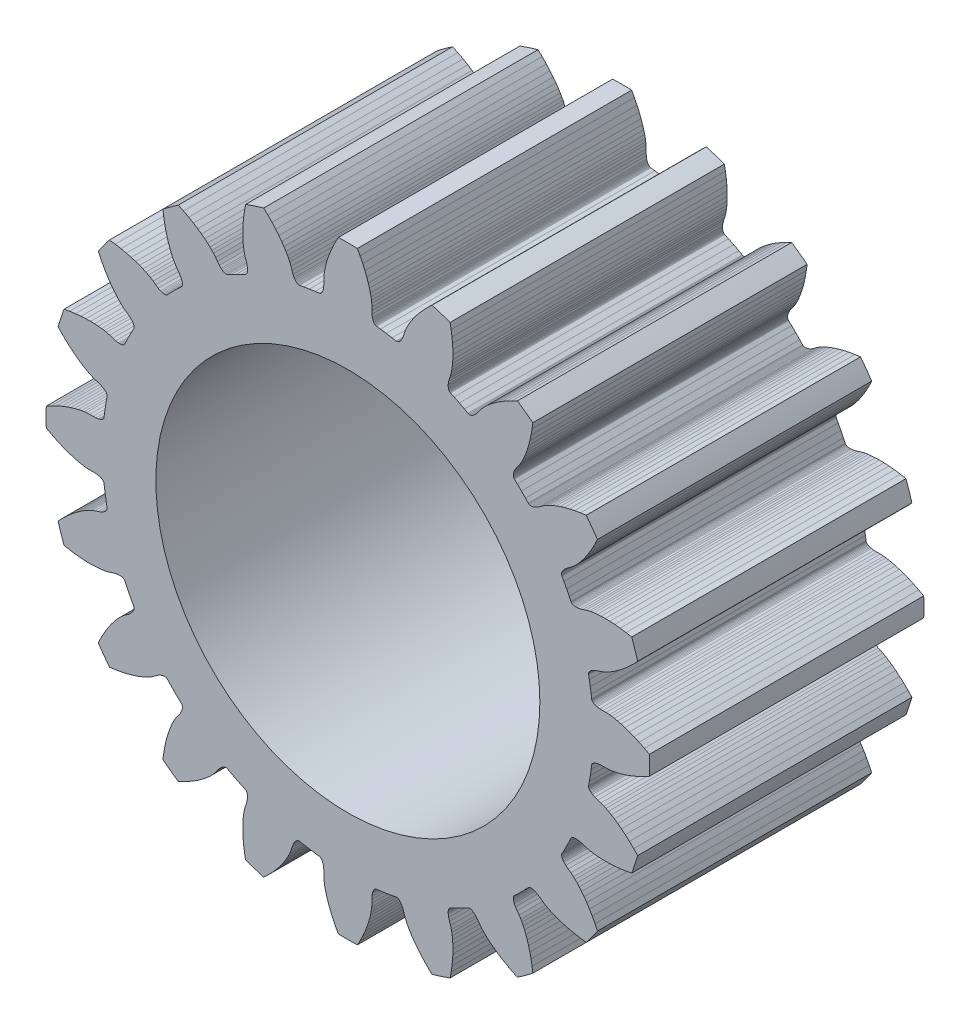
SolidWorks part; units mm, degrees
ref_plane "Front Plane" through (0, 0, 0) normal (0, 0, 1) x (1, 0, 0)
ref_plane "Top Plane" through (0, 0, 0) normal (0, 1, 0) x (1, 0, 0)
ref_plane "Right Plane" through (0, 0, 0) normal (1, 0, 0) x (0, 0, -1)
sketch "Model" plane through (0, 0, 0) normal (0, 0, 1) x (1, 0, 0)
  line L0 (10.4199, 2.9158) -> (10.2642, 2.7646)
  line L1 (10.2642, 2.7646) -> (10.1156, 2.6319)
  line L2 (10.1156, 2.6319) -> (9.974, 2.5157)
  line L3 (9.974, 2.5157) -> (9.8396, 2.4145)
  line L4 (9.8396, 2.4145) -> (9.7161, 2.3294)
  line L5 (9.7161, 2.3294) -> (9.602, 2.2576)
  line L6 (9.602, 2.2576) -> (9.5009, 2.1999)
  line L7 (9.5009, 2.1999) -> (9.4117, 2.1536)
  line L8 (9.4117, 2.1536) -> (9.3358, 2.1182)
  line L9 (9.3358, 2.1182) -> (9.2231, 2.0736)
  line L10 (9.2231, 2.0736) -> (9.1098, 2.0398)
  line L11 (9.1098, 2.0398) -> (9.0055, 2.0008)
  line L12 (9.0055, 2.0008) -> (8.9204, 1.9573)
  line L13 (8.9204, 1.9573) -> (8.8851, 1.9344)
  line L14 (8.8851, 1.9344) -> (8.8547, 1.9109)
  line L15 (8.8547, 1.9109) -> (8.8292, 1.8872)
  line L16 (8.8292, 1.8872) -> (8.8085, 1.8633)
  line L17 (8.8085, 1.8633) -> (8.7927, 1.8394)
  line L18 (8.7927, 1.8394) -> (8.7818, 1.8158)
  line L19 (8.7818, 1.8158) -> (8.7757, 1.7926)
  line L20 (8.7757, 1.7926) -> (8.7744, 1.7701)
  line L21 (8.7744, 1.7701) -> (8.7765, 1.7537)
  line L22 (8.7765, 1.7537) -> (8.8045, 1.6075)
  line L23 (8.8045, 1.6075) -> (8.8398, 1.4001)
  line L24 (8.8398, 1.4001) -> (8.8703, 1.1919)
  line L25 (8.8703, 1.1919) -> (8.8889, 1.0442)
  line L26 (8.8889, 1.0442) -> (8.8919, 1.028)
  line L27 (8.8919, 1.028) -> (8.9001, 1.0069)
  line L28 (8.9001, 1.0069) -> (8.9131, 0.9868)
  line L29 (8.9131, 0.9868) -> (8.9308, 0.9677)
  line L30 (8.9308, 0.9677) -> (8.9532, 0.9499)
  line L31 (8.9532, 0.9499) -> (8.9802, 0.9336)
  line L32 (8.9802, 0.9336) -> (9.0118, 0.9188)
  line L33 (9.0118, 0.9188) -> (9.048, 0.9059)
  line L34 (9.048, 0.9059) -> (9.0886, 0.895)
  line L35 (9.0886, 0.895) -> (9.183, 0.88)
  line L36 (9.183, 0.88) -> (9.2943, 0.8751)
  line L37 (9.2943, 0.8751) -> (9.4125, 0.878)
  line L38 (9.4125, 0.878) -> (9.5335, 0.8704)
  line L39 (9.5335, 0.8704) -> (9.6166, 0.8601)
  line L40 (9.6166, 0.8601) -> (9.7157, 0.8438)
  line L41 (9.7157, 0.8438) -> (9.8296, 0.82)
  line L42 (9.8296, 0.82) -> (9.9603, 0.787)
  line L43 (9.9603, 0.787) -> (10.1042, 0.7443)
  line L44 (10.1042, 0.7443) -> (10.2632, 0.6896)
  line L45 (10.2632, 0.6896) -> (10.4338, 0.6228)
  line L46 (10.4338, 0.6228) -> (10.6162, 0.5425)
  line L47 (10.6162, 0.5425) -> (10.8109, 0.4469)
  line L48 (10.8109, 0.4469) -> (10.9945, 0.3473)
  line L49 (10.9945, -0.3473) -> (10.8109, -0.4469)
  line L50 (10.8109, -0.4469) -> (10.6162, -0.5425)
  line L51 (10.6162, -0.5425) -> (10.4338, -0.6228)
  line L52 (10.4338, -0.6228) -> (10.2632, -0.6896)
  line L53 (10.2632, -0.6896) -> (10.1042, -0.7443)
  line L54 (10.1042, -0.7443) -> (9.9603, -0.787)
  line L55 (9.9603, -0.787) -> (9.8296, -0.82)
  line L56 (9.8296, -0.82) -> (9.7157, -0.8438)
  line L57 (9.7157, -0.8438) -> (9.6166, -0.8601)
  line L58 (9.6166, -0.8601) -> (9.5335, -0.8704)
  line L59 (9.5335, -0.8704) -> (9.4125, -0.878)
  line L60 (9.4125, -0.878) -> (9.2943, -0.8751)
  line L61 (9.2943, -0.8751) -> (9.183, -0.88)
  line L62 (9.183, -0.88) -> (9.0886, -0.895)
  line L63 (9.0886, -0.895) -> (9.048, -0.9059)
  line L64 (9.048, -0.9059) -> (9.0118, -0.9188)
  line L65 (9.0118, -0.9188) -> (8.9802, -0.9336)
  line L66 (8.9802, -0.9336) -> (8.9532, -0.9499)
  line L67 (8.9532, -0.9499) -> (8.9308, -0.9677)
  line L68 (8.9308, -0.9677) -> (8.9131, -0.9868)
  line L69 (8.9131, -0.9868) -> (8.9001, -1.0069)
  line L70 (8.9001, -1.0069) -> (8.8919, -1.028)
  line L71 (8.8919, -1.028) -> (8.8889, -1.0442)
  line L72 (8.8889, -1.0442) -> (8.8703, -1.1919)
  line L73 (8.8703, -1.1919) -> (8.8398, -1.4001)
  line L74 (8.8398, -1.4001) -> (8.8045, -1.6075)
  line L75 (8.8045, -1.6075) -> (8.7765, -1.7537)
  line L76 (8.7765, -1.7537) -> (8.7744, -1.7701)
  line L77 (8.7744, -1.7701) -> (8.7757, -1.7926)
  line L78 (8.7757, -1.7926) -> (8.7818, -1.8158)
  line L79 (8.7818, -1.8158) -> (8.7927, -1.8394)
  line L80 (8.7927, -1.8394) -> (8.8085, -1.8633)
  line L81 (8.8085, -1.8633) -> (8.8292, -1.8872)
  line L82 (8.8292, -1.8872) -> (8.8547, -1.9109)
  line L83 (8.8547, -1.9109) -> (8.8851, -1.9344)
  line L84 (8.8851, -1.9344) -> (8.9204, -1.9573)
  line L85 (8.9204, -1.9573) -> (9.0055, -2.0008)
  line L86 (9.0055, -2.0008) -> (9.1098, -2.0398)
  line L87 (9.1098, -2.0398) -> (9.2231, -2.0736)
  line L88 (9.2231, -2.0736) -> (9.3358, -2.1182)
  line L89 (9.3358, -2.1182) -> (9.4117, -2.1536)
  line L90 (9.4117, -2.1536) -> (9.5009, -2.1999)
  line L91 (9.5009, -2.1999) -> (9.602, -2.2576)
  line L92 (9.602, -2.2576) -> (9.7161, -2.3294)
  line L93 (9.7161, -2.3294) -> (9.8396, -2.4145)
  line L94 (9.8396, -2.4145) -> (9.974, -2.5157)
  line L95 (9.974, -2.5157) -> (10.1156, -2.6319)
  line L96 (10.1156, -2.6319) -> (10.2642, -2.7646)
  line L97 (10.2642, -2.7646) -> (10.4199, -2.9158)
  line L98 (10.4199, -2.9158) -> (10.5637, -3.0672)
  line L99 (10.3491, -3.7278) -> (10.1437, -3.7657)
  line L100 (10.1437, -3.7657) -> (9.9289, -3.7966)
  line L101 (9.9289, -3.7966) -> (9.7307, -3.8166)
  line L102 (9.7307, -3.8166) -> (9.5478, -3.8274)
  line L103 (9.5478, -3.8274) -> (9.3797, -3.8302)
  line L104 (9.3797, -3.8302) -> (9.2296, -3.8264)
  line L105 (9.2296, -3.8264) -> (9.0952, -3.8174)
  line L106 (9.0952, -3.8174) -> (8.9794, -3.8048)
  line L107 (8.9794, -3.8048) -> (8.8801, -3.7897)
  line L108 (8.8801, -3.7897) -> (8.7979, -3.7738)
  line L109 (8.7979, -3.7738) -> (8.6805, -3.7436)
  line L110 (8.6805, -3.7436) -> (8.569, -3.7044)
  line L111 (8.569, -3.7044) -> (8.4616, -3.6746)
  line L112 (8.4616, -3.6746) -> (8.3672, -3.6598)
  line L113 (8.3672, -3.6598) -> (8.3252, -3.6576)
  line L114 (8.3252, -3.6576) -> (8.2868, -3.6587)
  line L115 (8.2868, -3.6587) -> (8.2522, -3.6629)
  line L116 (8.2522, -3.6629) -> (8.2214, -3.6701)
  line L117 (8.2214, -3.6701) -> (8.1946, -3.6801)
  line L118 (8.1946, -3.6801) -> (8.1719, -3.6928)
  line L119 (8.1719, -3.6928) -> (8.1533, -3.7079)
  line L120 (8.1533, -3.7079) -> (8.139, -3.7254)
  line L121 (8.139, -3.7254) -> (8.1311, -3.7399)
  line L122 (8.1311, -3.7399) -> (8.0679, -3.8746)
  line L123 (8.0679, -3.8746) -> (7.9745, -4.0632)
  line L124 (7.9745, -4.0632) -> (7.8768, -4.2496)
  line L125 (7.8768, -4.2496) -> (7.805, -4.38)
  line L126 (7.805, -4.38) -> (7.7979, -4.3949)
  line L127 (7.7979, -4.3949) -> (7.7922, -4.4167)
  line L128 (7.7922, -4.4167) -> (7.7908, -4.4406)
  line L129 (7.7908, -4.4406) -> (7.794, -4.4665)
  line L130 (7.794, -4.4665) -> (7.8016, -4.494)
  line L131 (7.8016, -4.494) -> (7.8139, -4.5232)
  line L132 (7.8139, -4.5232) -> (7.8308, -4.5537)
  line L133 (7.8308, -4.5537) -> (7.8525, -4.5854)
  line L134 (7.8525, -4.5854) -> (7.8789, -4.618)
  line L135 (7.8789, -4.618) -> (7.9464, -4.6857)
  line L136 (7.9464, -4.6857) -> (8.0336, -4.7551)
  line L137 (8.0336, -4.7551) -> (8.1309, -4.8223)
  line L138 (8.1309, -4.8223) -> (8.2243, -4.8995)
  line L139 (8.2243, -4.8995) -> (8.2856, -4.9566)
  line L140 (8.2856, -4.9566) -> (8.3561, -5.0281)
  line L141 (8.3561, -5.0281) -> (8.4344, -5.1143)
  line L142 (8.4344, -5.1143) -> (8.5207, -5.2178)
  line L143 (8.5207, -5.2178) -> (8.6119, -5.337)
  line L144 (8.6119, -5.337) -> (8.7084, -5.4747)
  line L145 (8.7084, -5.4747) -> (8.8072, -5.629)
  line L146 (8.8072, -5.629) -> (8.9076, -5.8011)
  line L147 (8.9076, -5.8011) -> (9.0089, -5.993)
  line L148 (9.0089, -5.993) -> (9.0989, -6.1815)
  line L149 (8.6906, -6.7433) -> (8.4835, -6.716)
  line L150 (8.4835, -6.716) -> (8.2698, -6.6789)
  line L151 (8.2698, -6.6789) -> (8.0751, -6.6367)
  line L152 (8.0751, -6.6367) -> (7.8978, -6.5905)
  line L153 (7.8978, -6.5905) -> (7.737, -6.5412)
  line L154 (7.737, -6.5412) -> (7.5955, -6.4913)
  line L155 (7.5955, -6.4913) -> (7.4704, -6.4411)
  line L156 (7.4704, -6.4411) -> (7.3642, -6.3934)
  line L157 (7.3642, -6.3934) -> (7.2744, -6.3484)
  line L158 (7.2744, -6.3484) -> (7.2011, -6.3078)
  line L159 (7.2011, -6.3078) -> (7.0988, -6.2428)
  line L160 (7.0988, -6.2428) -> (7.0049, -6.171)
  line L161 (7.0049, -6.171) -> (6.9119, -6.1095)
  line L162 (6.9119, -6.1095) -> (6.8267, -6.0662)
  line L163 (6.8267, -6.0662) -> (6.7875, -6.0512)
  line L164 (6.7875, -6.0512) -> (6.7506, -6.0404)
  line L165 (6.7506, -6.0404) -> (6.7164, -6.0337)
  line L166 (6.7164, -6.0337) -> (6.6849, -6.031)
  line L167 (6.6849, -6.031) -> (6.6563, -6.0323)
  line L168 (6.6563, -6.0323) -> (6.6308, -6.0373)
  line L169 (6.6308, -6.0373) -> (6.6085, -6.046)
  line L170 (6.6085, -6.046) -> (6.5895, -6.0582)
  line L171 (6.5895, -6.0582) -> (6.5775, -6.0696)
  line L172 (6.5775, -6.0696) -> (6.4757, -6.1781)
  line L173 (6.4757, -6.1781) -> (6.3286, -6.3286)
  line L174 (6.3286, -6.3286) -> (6.1781, -6.4757)
  line L175 (6.1781, -6.4757) -> (6.0696, -6.5775)
  line L176 (6.0696, -6.5775) -> (6.0582, -6.5895)
  line L177 (6.0582, -6.5895) -> (6.046, -6.6085)
  line L178 (6.046, -6.6085) -> (6.0373, -6.6308)
  line L179 (6.0373, -6.6308) -> (6.0323, -6.6563)
  line L180 (6.0323, -6.6563) -> (6.031, -6.6849)
  line L181 (6.031, -6.6849) -> (6.0337, -6.7164)
  line L182 (6.0337, -6.7164) -> (6.0404, -6.7506)
  line L183 (6.0404, -6.7506) -> (6.0512, -6.7875)
  line L184 (6.0512, -6.7875) -> (6.0662, -6.8267)
  line L185 (6.0662, -6.8267) -> (6.1095, -6.9119)
  line L186 (6.1095, -6.9119) -> (6.171, -7.0049)
  line L187 (6.171, -7.0049) -> (6.2428, -7.0988)
  line L188 (6.2428, -7.0988) -> (6.3078, -7.2011)
  line L189 (6.3078, -7.2011) -> (6.3484, -7.2744)
  line L190 (6.3484, -7.2744) -> (6.3934, -7.3642)
  line L191 (6.3934, -7.3642) -> (6.4411, -7.4704)
  line L192 (6.4411, -7.4704) -> (6.4913, -7.5955)
  line L193 (6.4913, -7.5955) -> (6.5412, -7.737)
  line L194 (6.5412, -7.737) -> (6.5905, -7.8978)
  line L195 (6.5905, -7.8978) -> (6.6367, -8.0751)
  line L196 (6.6367, -8.0751) -> (6.6789, -8.2698)
  line L197 (6.6789, -8.2698) -> (6.716, -8.4835)
  line L198 (6.716, -8.4835) -> (6.7433, -8.6906)
  line L199 (6.1815, -9.0989) -> (5.993, -9.0089)
  line L200 (5.993, -9.0089) -> (5.8011, -8.9076)
  line L201 (5.8011, -8.9076) -> (5.629, -8.8072)
  line L202 (5.629, -8.8072) -> (5.4747, -8.7084)
  line L203 (5.4747, -8.7084) -> (5.337, -8.6119)
  line L204 (5.337, -8.6119) -> (5.2178, -8.5207)
  line L205 (5.2178, -8.5207) -> (5.1143, -8.4344)
  line L206 (5.1143, -8.4344) -> (5.0281, -8.3561)
  line L207 (5.0281, -8.3561) -> (4.9566, -8.2856)
  line L208 (4.9566, -8.2856) -> (4.8995, -8.2243)
  line L209 (4.8995, -8.2243) -> (4.8223, -8.1309)
  line L210 (4.8223, -8.1309) -> (4.7551, -8.0336)
  line L211 (4.7551, -8.0336) -> (4.6857, -7.9464)
  line L212 (4.6857, -7.9464) -> (4.618, -7.8789)
  line L213 (4.618, -7.8789) -> (4.5854, -7.8525)
  line L214 (4.5854, -7.8525) -> (4.5537, -7.8308)
  line L215 (4.5537, -7.8308) -> (4.5232, -7.8139)
  line L216 (4.5232, -7.8139) -> (4.494, -7.8016)
  line L217 (4.494, -7.8016) -> (4.4665, -7.794)
  line L218 (4.4665, -7.794) -> (4.4406, -7.7908)
  line L219 (4.4406, -7.7908) -> (4.4167, -7.7922)
  line L220 (4.4167, -7.7922) -> (4.3949, -7.7979)
  line L221 (4.3949, -7.7979) -> (4.38, -7.805)
  line L222 (4.38, -7.805) -> (4.2496, -7.8768)
  line L223 (4.2496, -7.8768) -> (4.0632, -7.9745)
  line L224 (4.0632, -7.9745) -> (3.8746, -8.0679)
  line L225 (3.8746, -8.0679) -> (3.7399, -8.1311)
  line L226 (3.7399, -8.1311) -> (3.7254, -8.139)
  line L227 (3.7254, -8.139) -> (3.7079, -8.1533)
  line L228 (3.7079, -8.1533) -> (3.6928, -8.1719)
  line L229 (3.6928, -8.1719) -> (3.6801, -8.1946)
  line L230 (3.6801, -8.1946) -> (3.6701, -8.2214)
  line L231 (3.6701, -8.2214) -> (3.6629, -8.2522)
  line L232 (3.6629, -8.2522) -> (3.6587, -8.2868)
  line L233 (3.6587, -8.2868) -> (3.6576, -8.3252)
  line L234 (3.6576, -8.3252) -> (3.6598, -8.3672)
  line L235 (3.6598, -8.3672) -> (3.6746, -8.4616)
  line L236 (3.6746, -8.4616) -> (3.7044, -8.569)
  line L237 (3.7044, -8.569) -> (3.7436, -8.6805)
  line L238 (3.7436, -8.6805) -> (3.7738, -8.7979)
  line L239 (3.7738, -8.7979) -> (3.7897, -8.8801)
  line L240 (3.7897, -8.8801) -> (3.8048, -8.9794)
  line L241 (3.8048, -8.9794) -> (3.8174, -9.0952)
  line L242 (3.8174, -9.0952) -> (3.8264, -9.2296)
  line L243 (3.8264, -9.2296) -> (3.8302, -9.3797)
  line L244 (3.8302, -9.3797) -> (3.8274, -9.5478)
  line L245 (3.8274, -9.5478) -> (3.8166, -9.7307)
  line L246 (3.8166, -9.7307) -> (3.7966, -9.9289)
  line L247 (3.7966, -9.9289) -> (3.7657, -10.1437)
  line L248 (3.7657, -10.1437) -> (3.7278, -10.3491)
  line L249 (3.0672, -10.5637) -> (2.9158, -10.4199)
  line L250 (2.9158, -10.4199) -> (2.7646, -10.2642)
  line L251 (2.7646, -10.2642) -> (2.6319, -10.1156)
  line L252 (2.6319, -10.1156) -> (2.5157, -9.974)
  line L253 (2.5157, -9.974) -> (2.4145, -9.8396)
  line L254 (2.4145, -9.8396) -> (2.3294, -9.7161)
  line L255 (2.3294, -9.7161) -> (2.2576, -9.602)
  line L256 (2.2576, -9.602) -> (2.1999, -9.5009)
  line L257 (2.1999, -9.5009) -> (2.1536, -9.4117)
  line L258 (2.1536, -9.4117) -> (2.1182, -9.3358)
  line L259 (2.1182, -9.3358) -> (2.0736, -9.2231)
  line L260 (2.0736, -9.2231) -> (2.0398, -9.1098)
  line L261 (2.0398, -9.1098) -> (2.0008, -9.0055)
  line L262 (2.0008, -9.0055) -> (1.9573, -8.9204)
  line L263 (1.9573, -8.9204) -> (1.9344, -8.8851)
  line L264 (1.9344, -8.8851) -> (1.9109, -8.8547)
  line L265 (1.9109, -8.8547) -> (1.8872, -8.8292)
  line L266 (1.8872, -8.8292) -> (1.8633, -8.8085)
  line L267 (1.8633, -8.8085) -> (1.8394, -8.7927)
  line L268 (1.8394, -8.7927) -> (1.8158, -8.7818)
  line L269 (1.8158, -8.7818) -> (1.7926, -8.7757)
  line L270 (1.7926, -8.7757) -> (1.7701, -8.7744)
  line L271 (1.7701, -8.7744) -> (1.7537, -8.7765)
  line L272 (1.7537, -8.7765) -> (1.6075, -8.8045)
  line L273 (1.6075, -8.8045) -> (1.4001, -8.8398)
  line L274 (1.4001, -8.8398) -> (1.1919, -8.8703)
  line L275 (1.1919, -8.8703) -> (1.0442, -8.8889)
  line L276 (1.0442, -8.8889) -> (1.028, -8.8919)
  line L277 (1.028, -8.8919) -> (1.0069, -8.9001)
  line L278 (1.0069, -8.9001) -> (0.9868, -8.9131)
  line L279 (0.9868, -8.9131) -> (0.9677, -8.9308)
  line L280 (0.9677, -8.9308) -> (0.9499, -8.9532)
  line L281 (0.9499, -8.9532) -> (0.9336, -8.9802)
  line L282 (0.9336, -8.9802) -> (0.9188, -9.0118)
  line L283 (0.9188, -9.0118) -> (0.9059, -9.048)
  line L284 (0.9059, -9.048) -> (0.895, -9.0886)
  line L285 (0.895, -9.0886) -> (0.88, -9.183)
  line L286 (0.88, -9.183) -> (0.8751, -9.2943)
  line L287 (0.8751, -9.2943) -> (0.878, -9.4125)
  line L288 (0.878, -9.4125) -> (0.8704, -9.5335)
  line L289 (0.8704, -9.5335) -> (0.8601, -9.6166)
  line L290 (0.8601, -9.6166) -> (0.8438, -9.7157)
  line L291 (0.8438, -9.7157) -> (0.82, -9.8296)
  line L292 (0.82, -9.8296) -> (0.787, -9.9603)
  line L293 (0.787, -9.9603) -> (0.7443, -10.1042)
  line L294 (0.7443, -10.1042) -> (0.6896, -10.2632)
  line L295 (0.6896, -10.2632) -> (0.6228, -10.4338)
  line L296 (0.6228, -10.4338) -> (0.5425, -10.6162)
  line L297 (0.5425, -10.6162) -> (0.4469, -10.8109)
  line L298 (0.4469, -10.8109) -> (0.3473, -10.9945)
  line L299 (-0.3473, -10.9945) -> (-0.4469, -10.8109)
  line L300 (-0.4469, -10.8109) -> (-0.5425, -10.6162)
  line L301 (-0.5425, -10.6162) -> (-0.6228, -10.4338)
  line L302 (-0.6228, -10.4338) -> (-0.6896, -10.2632)
  line L303 (-0.6896, -10.2632) -> (-0.7443, -10.1042)
  line L304 (-0.7443, -10.1042) -> (-0.787, -9.9603)
  line L305 (-0.787, -9.9603) -> (-0.82, -9.8296)
  line L306 (-0.82, -9.8296) -> (-0.8438, -9.7157)
  line L307 (-0.8438, -9.7157) -> (-0.8601, -9.6166)
  line L308 (-0.8601, -9.6166) -> (-0.8704, -9.5335)
  line L309 (-0.8704, -9.5335) -> (-0.878, -9.4125)
  line L310 (-0.878, -9.4125) -> (-0.8751, -9.2943)
  line L311 (-0.8751, -9.2943) -> (-0.88, -9.183)
  line L312 (-0.88, -9.183) -> (-0.895, -9.0886)
  line L313 (-0.895, -9.0886) -> (-0.9059, -9.048)
  line L314 (-0.9059, -9.048) -> (-0.9188, -9.0118)
  line L315 (-0.9188, -9.0118) -> (-0.9336, -8.9802)
  line L316 (-0.9336, -8.9802) -> (-0.9499, -8.9532)
  line L317 (-0.9499, -8.9532) -> (-0.9677, -8.9308)
  line L318 (-0.9677, -8.9308) -> (-0.9868, -8.9131)
  line L319 (-0.9868, -8.9131) -> (-1.0069, -8.9001)
  line L320 (-1.0069, -8.9001) -> (-1.028, -8.8919)
  line L321 (-1.028, -8.8919) -> (-1.0442, -8.8889)
  line L322 (-1.0442, -8.8889) -> (-1.1919, -8.8703)
  line L323 (-1.1919, -8.8703) -> (-1.4001, -8.8398)
  line L324 (-1.4001, -8.8398) -> (-1.6075, -8.8045)
  line L325 (-1.6075, -8.8045) -> (-1.7537, -8.7765)
  line L326 (-1.7537, -8.7765) -> (-1.7701, -8.7744)
  line L327 (-1.7701, -8.7744) -> (-1.7926, -8.7757)
  line L328 (-1.7926, -8.7757) -> (-1.8158, -8.7818)
  line L329 (-1.8158, -8.7818) -> (-1.8394, -8.7927)
  line L330 (-1.8394, -8.7927) -> (-1.8633, -8.8085)
  line L331 (-1.8633, -8.8085) -> (-1.8872, -8.8292)
  line L332 (-1.8872, -8.8292) -> (-1.9109, -8.8547)
  line L333 (-1.9109, -8.8547) -> (-1.9344, -8.8851)
  line L334 (-1.9344, -8.8851) -> (-1.9573, -8.9204)
  line L335 (-1.9573, -8.9204) -> (-2.0008, -9.0055)
  line L336 (-2.0008, -9.0055) -> (-2.0398, -9.1098)
  line L337 (-2.0398, -9.1098) -> (-2.0736, -9.2231)
  line L338 (-2.0736, -9.2231) -> (-2.1182, -9.3358)
  line L339 (-2.1182, -9.3358) -> (-2.1536, -9.4117)
  line L340 (-2.1536, -9.4117) -> (-2.1999, -9.5009)
  line L341 (-2.1999, -9.5009) -> (-2.2576, -9.602)
  line L342 (-2.2576, -9.602) -> (-2.3294, -9.7161)
  line L343 (-2.3294, -9.7161) -> (-2.4145, -9.8396)
  line L344 (-2.4145, -9.8396) -> (-2.5157, -9.974)
  line L345 (-2.5157, -9.974) -> (-2.6319, -10.1156)
  line L346 (-2.6319, -10.1156) -> (-2.7646, -10.2642)
  line L347 (-2.7646, -10.2642) -> (-2.9158, -10.4199)
  line L348 (-2.9158, -10.4199) -> (-3.0672, -10.5637)
  line L349 (-3.7278, -10.3491) -> (-3.7657, -10.1437)
  line L350 (-3.7657, -10.1437) -> (-3.7966, -9.9289)
  line L351 (-3.7966, -9.9289) -> (-3.8166, -9.7307)
  line L352 (-3.8166, -9.7307) -> (-3.8274, -9.5478)
  line L353 (-3.8274, -9.5478) -> (-3.8302, -9.3797)
  line L354 (-3.8302, -9.3797) -> (-3.8264, -9.2296)
  line L355 (-3.8264, -9.2296) -> (-3.8174, -9.0952)
  line L356 (-3.8174, -9.0952) -> (-3.8048, -8.9794)
  line L357 (-3.8048, -8.9794) -> (-3.7897, -8.8801)
  line L358 (-3.7897, -8.8801) -> (-3.7738, -8.7979)
  line L359 (-3.7738, -8.7979) -> (-3.7436, -8.6805)
  line L360 (-3.7436, -8.6805) -> (-3.7044, -8.569)
  line L361 (-3.7044, -8.569) -> (-3.6746, -8.4616)
  line L362 (-3.6746, -8.4616) -> (-3.6598, -8.3672)
  line L363 (-3.6598, -8.3672) -> (-3.6576, -8.3252)
  line L364 (-3.6576, -8.3252) -> (-3.6587, -8.2868)
  line L365 (-3.6587, -8.2868) -> (-3.6629, -8.2522)
  line L366 (-3.6629, -8.2522) -> (-3.6701, -8.2214)
  line L367 (-3.6701, -8.2214) -> (-3.6801, -8.1946)
  line L368 (-3.6801, -8.1946) -> (-3.6928, -8.1719)
  line L369 (-3.6928, -8.1719) -> (-3.7079, -8.1533)
  line L370 (-3.7079, -8.1533) -> (-3.7254, -8.139)
  line L371 (-3.7254, -8.139) -> (-3.7399, -8.1311)
  line L372 (-3.7399, -8.1311) -> (-3.8746, -8.0679)
  line L373 (-3.8746, -8.0679) -> (-4.0632, -7.9745)
  line L374 (-4.0632, -7.9745) -> (-4.2496, -7.8768)
  line L375 (-4.2496, -7.8768) -> (-4.38, -7.805)
  line L376 (-4.38, -7.805) -> (-4.3949, -7.7979)
  line L377 (-4.3949, -7.7979) -> (-4.4167, -7.7922)
  line L378 (-4.4167, -7.7922) -> (-4.4406, -7.7908)
  line L379 (-4.4406, -7.7908) -> (-4.4665, -7.794)
  line L380 (-4.4665, -7.794) -> (-4.494, -7.8016)
  line L381 (-4.494, -7.8016) -> (-4.5232, -7.8139)
  line L382 (-4.5232, -7.8139) -> (-4.5537, -7.8308)
  line L383 (-4.5537, -7.8308) -> (-4.5854, -7.8525)
  line L384 (-4.5854, -7.8525) -> (-4.618, -7.8789)
  line L385 (-4.618, -7.8789) -> (-4.6857, -7.9464)
  line L386 (-4.6857, -7.9464) -> (-4.7551, -8.0336)
  line L387 (-4.7551, -8.0336) -> (-4.8223, -8.1309)
  line L388 (-4.8223, -8.1309) -> (-4.8995, -8.2243)
  line L389 (-4.8995, -8.2243) -> (-4.9566, -8.2856)
  line L390 (-4.9566, -8.2856) -> (-5.0281, -8.3561)
  line L391 (-5.0281, -8.3561) -> (-5.1143, -8.4344)
  line L392 (-5.1143, -8.4344) -> (-5.2178, -8.5207)
  line L393 (-5.2178, -8.5207) -> (-5.337, -8.6119)
  line L394 (-5.337, -8.6119) -> (-5.4747, -8.7084)
  line L395 (-5.4747, -8.7084) -> (-5.629, -8.8072)
  line L396 (-5.629, -8.8072) -> (-5.8011, -8.9076)
  line L397 (-5.8011, -8.9076) -> (-5.993, -9.0089)
  line L398 (-5.993, -9.0089) -> (-6.1815, -9.0989)
  line L399 (-6.7433, -8.6906) -> (-6.716, -8.4835)
  line L400 (-6.716, -8.4835) -> (-6.6789, -8.2698)
  line L401 (-6.6789, -8.2698) -> (-6.6367, -8.0751)
  line L402 (-6.6367, -8.0751) -> (-6.5905, -7.8978)
  line L403 (-6.5905, -7.8978) -> (-6.5412, -7.737)
  line L404 (-6.5412, -7.737) -> (-6.4913, -7.5955)
  line L405 (-6.4913, -7.5955) -> (-6.4411, -7.4704)
  line L406 (-6.4411, -7.4704) -> (-6.3934, -7.3642)
  line L407 (-6.3934, -7.3642) -> (-6.3484, -7.2744)
  line L408 (-6.3484, -7.2744) -> (-6.3078, -7.2011)
  line L409 (-6.3078, -7.2011) -> (-6.2428, -7.0988)
  line L410 (-6.2428, -7.0988) -> (-6.171, -7.0049)
  line L411 (-6.171, -7.0049) -> (-6.1095, -6.9119)
  line L412 (-6.1095, -6.9119) -> (-6.0662, -6.8267)
  line L413 (-6.0662, -6.8267) -> (-6.0512, -6.7875)
  line L414 (-6.0512, -6.7875) -> (-6.0404, -6.7506)
  line L415 (-6.0404, -6.7506) -> (-6.0337, -6.7164)
  line L416 (-6.0337, -6.7164) -> (-6.031, -6.6849)
  line L417 (-6.031, -6.6849) -> (-6.0323, -6.6563)
  line L418 (-6.0323, -6.6563) -> (-6.0373, -6.6308)
  line L419 (-6.0373, -6.6308) -> (-6.046, -6.6085)
  line L420 (-6.046, -6.6085) -> (-6.0582, -6.5895)
  line L421 (-6.0582, -6.5895) -> (-6.0696, -6.5775)
  line L422 (-6.0696, -6.5775) -> (-6.1781, -6.4757)
  line L423 (-6.1781, -6.4757) -> (-6.3286, -6.3286)
  line L424 (-6.3286, -6.3286) -> (-6.4757, -6.1781)
  line L425 (-6.4757, -6.1781) -> (-6.5775, -6.0696)
  line L426 (-6.5775, -6.0696) -> (-6.5895, -6.0582)
  line L427 (-6.5895, -6.0582) -> (-6.6085, -6.046)
  line L428 (-6.6085, -6.046) -> (-6.6308, -6.0373)
  line L429 (-6.6308, -6.0373) -> (-6.6563, -6.0323)
  line L430 (-6.6563, -6.0323) -> (-6.6849, -6.031)
  line L431 (-6.6849, -6.031) -> (-6.7164, -6.0337)
  line L432 (-6.7164, -6.0337) -> (-6.7506, -6.0404)
  line L433 (-6.7506, -6.0404) -> (-6.7875, -6.0512)
  line L434 (-6.7875, -6.0512) -> (-6.8267, -6.0662)
  line L435 (-6.8267, -6.0662) -> (-6.9119, -6.1095)
  line L436 (-6.9119, -6.1095) -> (-7.0049, -6.171)
  line L437 (-7.0049, -6.171) -> (-7.0988, -6.2428)
  line L438 (-7.0988, -6.2428) -> (-7.2011, -6.3078)
  line L439 (-7.2011, -6.3078) -> (-7.2744, -6.3484)
  line L440 (-7.2744, -6.3484) -> (-7.3642, -6.3934)
  line L441 (-7.3642, -6.3934) -> (-7.4704, -6.4411)
  line L442 (-7.4704, -6.4411) -> (-7.5955, -6.4913)
  line L443 (-7.5955, -6.4913) -> (-7.737, -6.5412)
  line L444 (-7.737, -6.5412) -> (-7.8978, -6.5905)
  line L445 (-7.8978, -6.5905) -> (-8.0751, -6.6367)
  line L446 (-8.0751, -6.6367) -> (-8.2698, -6.6789)
  line L447 (-8.2698, -6.6789) -> (-8.4835, -6.716)
  line L448 (-8.4835, -6.716) -> (-8.6906, -6.7433)
  line L449 (-9.0989, -6.1815) -> (-9.0089, -5.993)
  line L450 (-9.0089, -5.993) -> (-8.9076, -5.8011)
  line L451 (-8.9076, -5.8011) -> (-8.8072, -5.629)
  line L452 (-8.8072, -5.629) -> (-8.7084, -5.4747)
  line L453 (-8.7084, -5.4747) -> (-8.6119, -5.337)
  line L454 (-8.6119, -5.337) -> (-8.5207, -5.2178)
  line L455 (-8.5207, -5.2178) -> (-8.4344, -5.1143)
  line L456 (-8.4344, -5.1143) -> (-8.3561, -5.0281)
  line L457 (-8.3561, -5.0281) -> (-8.2856, -4.9566)
  line L458 (-8.2856, -4.9566) -> (-8.2243, -4.8995)
  line L459 (-8.2243, -4.8995) -> (-8.1309, -4.8223)
  line L460 (-8.1309, -4.8223) -> (-8.0336, -4.7551)
  line L461 (-8.0336, -4.7551) -> (-7.9464, -4.6857)
  line L462 (-7.9464, -4.6857) -> (-7.8789, -4.618)
  line L463 (-7.8789, -4.618) -> (-7.8525, -4.5854)
  line L464 (-7.8525, -4.5854) -> (-7.8308, -4.5537)
  line L465 (-7.8308, -4.5537) -> (-7.8139, -4.5232)
  line L466 (-7.8139, -4.5232) -> (-7.8016, -4.494)
  line L467 (-7.8016, -4.494) -> (-7.794, -4.4665)
  line L468 (-7.794, -4.4665) -> (-7.7908, -4.4406)
  line L469 (-7.7908, -4.4406) -> (-7.7922, -4.4167)
  line L470 (-7.7922, -4.4167) -> (-7.7979, -4.3949)
  line L471 (-7.7979, -4.3949) -> (-7.805, -4.38)
  line L472 (-7.805, -4.38) -> (-7.8768, -4.2496)
  line L473 (-7.8768, -4.2496) -> (-7.9745, -4.0632)
  line L474 (-7.9745, -4.0632) -> (-8.0679, -3.8746)
  line L475 (-8.0679, -3.8746) -> (-8.1311, -3.7399)
  line L476 (-8.1311, -3.7399) -> (-8.139, -3.7254)
  line L477 (-8.139, -3.7254) -> (-8.1533, -3.7079)
  line L478 (-8.1533, -3.7079) -> (-8.1719, -3.6928)
  line L479 (-8.1719, -3.6928) -> (-8.1946, -3.6801)
  line L480 (-8.1946, -3.6801) -> (-8.2214, -3.6701)
  line L481 (-8.2214, -3.6701) -> (-8.2522, -3.6629)
  line L482 (-8.2522, -3.6629) -> (-8.2868, -3.6587)
  line L483 (-8.2868, -3.6587) -> (-8.3252, -3.6576)
  line L484 (-8.3252, -3.6576) -> (-8.3672, -3.6598)
  line L485 (-8.3672, -3.6598) -> (-8.4616, -3.6746)
  line L486 (-8.4616, -3.6746) -> (-8.569, -3.7044)
  line L487 (-8.569, -3.7044) -> (-8.6805, -3.7436)
  line L488 (-8.6805, -3.7436) -> (-8.7979, -3.7738)
  line L489 (-8.7979, -3.7738) -> (-8.8801, -3.7897)
  line L490 (-8.8801, -3.7897) -> (-8.9794, -3.8048)
  line L491 (-8.9794, -3.8048) -> (-9.0952, -3.8174)
  line L492 (-9.0952, -3.8174) -> (-9.2296, -3.8264)
  line L493 (-9.2296, -3.8264) -> (-9.3797, -3.8302)
  line L494 (-9.3797, -3.8302) -> (-9.5478, -3.8274)
  line L495 (-9.5478, -3.8274) -> (-9.7307, -3.8166)
  line L496 (-9.7307, -3.8166) -> (-9.9289, -3.7966)
  line L497 (-9.9289, -3.7966) -> (-10.1437, -3.7657)
  line L498 (-10.1437, -3.7657) -> (-10.3491, -3.7278)
  line L499 (-10.5637, -3.0672) -> (-10.4199, -2.9158)
  line L500 (-10.4199, -2.9158) -> (-10.2642, -2.7646)
  line L501 (-10.2642, -2.7646) -> (-10.1156, -2.6319)
  line L502 (-10.1156, -2.6319) -> (-9.974, -2.5157)
  line L503 (-9.974, -2.5157) -> (-9.8396, -2.4145)
  line L504 (-9.8396, -2.4145) -> (-9.7161, -2.3294)
  line L505 (-9.7161, -2.3294) -> (-9.602, -2.2576)
  line L506 (-9.602, -2.2576) -> (-9.5009, -2.1999)
  line L507 (-9.5009, -2.1999) -> (-9.4117, -2.1536)
  line L508 (-9.4117, -2.1536) -> (-9.3358, -2.1182)
  line L509 (-9.3358, -2.1182) -> (-9.2231, -2.0736)
  line L510 (-9.2231, -2.0736) -> (-9.1098, -2.0398)
  line L511 (-9.1098, -2.0398) -> (-9.0055, -2.0008)
  line L512 (-9.0055, -2.0008) -> (-8.9204, -1.9573)
  line L513 (-8.9204, -1.9573) -> (-8.8851, -1.9344)
  line L514 (-8.8851, -1.9344) -> (-8.8547, -1.9109)
  line L515 (-8.8547, -1.9109) -> (-8.8292, -1.8872)
  line L516 (-8.8292, -1.8872) -> (-8.8085, -1.8633)
  line L517 (-8.8085, -1.8633) -> (-8.7927, -1.8394)
  line L518 (-8.7927, -1.8394) -> (-8.7818, -1.8158)
  line L519 (-8.7818, -1.8158) -> (-8.7757, -1.7926)
  line L520 (-8.7757, -1.7926) -> (-8.7744, -1.7701)
  line L521 (-8.7744, -1.7701) -> (-8.7765, -1.7537)
  line L522 (-8.7765, -1.7537) -> (-8.8045, -1.6075)
  line L523 (-8.8045, -1.6075) -> (-8.8398, -1.4001)
  line L524 (-8.8398, -1.4001) -> (-8.8703, -1.1919)
  line L525 (-8.8703, -1.1919) -> (-8.8889, -1.0442)
  line L526 (-8.8889, -1.0442) -> (-8.8919, -1.028)
  line L527 (-8.8919, -1.028) -> (-8.9001, -1.0069)
  line L528 (-8.9001, -1.0069) -> (-8.9131, -0.9868)
  line L529 (-8.9131, -0.9868) -> (-8.9308, -0.9677)
  line L530 (-8.9308, -0.9677) -> (-8.9532, -0.9499)
  line L531 (-8.9532, -0.9499) -> (-8.9802, -0.9336)
  line L532 (-8.9802, -0.9336) -> (-9.0118, -0.9188)
  line L533 (-9.0118, -0.9188) -> (-9.048, -0.9059)
  line L534 (-9.048, -0.9059) -> (-9.0886, -0.895)
  line L535 (-9.0886, -0.895) -> (-9.183, -0.88)
  line L536 (-9.183, -0.88) -> (-9.2943, -0.8751)
  line L537 (-9.2943, -0.8751) -> (-9.4125, -0.878)
  line L538 (-9.4125, -0.878) -> (-9.5335, -0.8704)
  line L539 (-9.5335, -0.8704) -> (-9.6166, -0.8601)
  line L540 (-9.6166, -0.8601) -> (-9.7157, -0.8438)
  line L541 (-9.7157, -0.8438) -> (-9.8296, -0.82)
  line L542 (-9.8296, -0.82) -> (-9.9603, -0.787)
  line L543 (-9.9603, -0.787) -> (-10.1042, -0.7443)
  line L544 (-10.1042, -0.7443) -> (-10.2632, -0.6896)
  line L545 (-10.2632, -0.6896) -> (-10.4338, -0.6228)
  line L546 (-10.4338, -0.6228) -> (-10.6162, -0.5425)
  line L547 (-10.6162, -0.5425) -> (-10.8109, -0.4469)
  line L548 (-10.8109, -0.4469) -> (-10.9945, -0.3473)
  line L549 (-10.9945, 0.3473) -> (-10.8109, 0.4469)
  line L550 (-10.8109, 0.4469) -> (-10.6162, 0.5425)
  line L551 (-10.6162, 0.5425) -> (-10.4338, 0.6228)
  line L552 (-10.4338, 0.6228) -> (-10.2632, 0.6896)
  line L553 (-10.2632, 0.6896) -> (-10.1042, 0.7443)
  line L554 (-10.1042, 0.7443) -> (-9.9603, 0.787)
  line L555 (-9.9603, 0.787) -> (-9.8296, 0.82)
  line L556 (-9.8296, 0.82) -> (-9.7157, 0.8438)
  line L557 (-9.7157, 0.8438) -> (-9.6166, 0.8601)
  line L558 (-9.6166, 0.8601) -> (-9.5335, 0.8704)
  line L559 (-9.5335, 0.8704) -> (-9.4125, 0.878)
  line L560 (-9.4125, 0.878) -> (-9.2943, 0.8751)
  line L561 (-9.2943, 0.8751) -> (-9.183, 0.88)
  line L562 (-9.183, 0.88) -> (-9.0886, 0.895)
  line L563 (-9.0886, 0.895) -> (-9.048, 0.9059)
  line L564 (-9.048, 0.9059) -> (-9.0118, 0.9188)
  line L565 (-9.0118, 0.9188) -> (-8.9802, 0.9336)
  line L566 (-8.9802, 0.9336) -> (-8.9532, 0.9499)
  line L567 (-8.9532, 0.9499) -> (-8.9308, 0.9677)
  line L568 (-8.9308, 0.9677) -> (-8.9131, 0.9868)
  line L569 (-8.9131, 0.9868) -> (-8.9001, 1.0069)
  line L570 (-8.9001, 1.0069) -> (-8.8919, 1.028)
  line L571 (-8.8919, 1.028) -> (-8.8889, 1.0442)
  line L572 (-8.8889, 1.0442) -> (-8.8703, 1.1919)
  line L573 (-8.8703, 1.1919) -> (-8.8398, 1.4001)
  line L574 (-8.8398, 1.4001) -> (-8.8045, 1.6075)
  line L575 (-8.8045, 1.6075) -> (-8.7765, 1.7537)
  line L576 (-8.7765, 1.7537) -> (-8.7744, 1.7701)
  line L577 (-8.7744, 1.7701) -> (-8.7757, 1.7926)
  line L578 (-8.7757, 1.7926) -> (-8.7818, 1.8158)
  line L579 (-8.7818, 1.8158) -> (-8.7927, 1.8394)
  line L580 (-8.7927, 1.8394) -> (-8.8085, 1.8633)
  line L581 (-8.8085, 1.8633) -> (-8.8292, 1.8872)
  line L582 (-8.8292, 1.8872) -> (-8.8547, 1.9109)
  line L583 (-8.8547, 1.9109) -> (-8.8851, 1.9344)
  line L584 (-8.8851, 1.9344) -> (-8.9204, 1.9573)
  line L585 (-8.9204, 1.9573) -> (-9.0055, 2.0008)
  line L586 (-9.0055, 2.0008) -> (-9.1098, 2.0398)
  line L587 (-9.1098, 2.0398) -> (-9.2231, 2.0736)
  line L588 (-9.2231, 2.0736) -> (-9.3358, 2.1182)
  line L589 (-9.3358, 2.1182) -> (-9.4117, 2.1536)
  line L590 (-9.4117, 2.1536) -> (-9.5009, 2.1999)
  line L591 (-9.5009, 2.1999) -> (-9.602, 2.2576)
  line L592 (-9.602, 2.2576) -> (-9.7161, 2.3294)
  line L593 (-9.7161, 2.3294) -> (-9.8396, 2.4145)
  line L594 (-9.8396, 2.4145) -> (-9.974, 2.5157)
  line L595 (-9.974, 2.5157) -> (-10.1156, 2.6319)
  line L596 (-10.1156, 2.6319) -> (-10.2642, 2.7646)
  line L597 (-10.2642, 2.7646) -> (-10.4199, 2.9158)
  line L598 (-10.4199, 2.9158) -> (-10.5637, 3.0672)
  line L599 (-10.3491, 3.7278) -> (-10.1437, 3.7657)
  line L600 (-10.1437, 3.7657) -> (-9.9289, 3.7966)
  line L601 (-9.9289, 3.7966) -> (-9.7307, 3.8166)
  line L602 (-9.7307, 3.8166) -> (-9.5478, 3.8274)
  line L603 (-9.5478, 3.8274) -> (-9.3797, 3.8302)
  line L604 (-9.3797, 3.8302) -> (-9.2296, 3.8264)
  line L605 (-9.2296, 3.8264) -> (-9.0952, 3.8174)
  line L606 (-9.0952, 3.8174) -> (-8.9794, 3.8048)
  line L607 (-8.9794, 3.8048) -> (-8.8801, 3.7897)
  line L608 (-8.8801, 3.7897) -> (-8.7979, 3.7738)
  line L609 (-8.7979, 3.7738) -> (-8.6805, 3.7436)
  line L610 (-8.6805, 3.7436) -> (-8.569, 3.7044)
  line L611 (-8.569, 3.7044) -> (-8.4616, 3.6746)
  line L612 (-8.4616, 3.6746) -> (-8.3672, 3.6598)
  line L613 (-8.3672, 3.6598) -> (-8.3252, 3.6576)
  line L614 (-8.3252, 3.6576) -> (-8.2868, 3.6587)
  line L615 (-8.2868, 3.6587) -> (-8.2522, 3.6629)
  line L616 (-8.2522, 3.6629) -> (-8.2214, 3.6701)
  line L617 (-8.2214, 3.6701) -> (-8.1946, 3.6801)
  line L618 (-8.1946, 3.6801) -> (-8.1719, 3.6928)
  line L619 (-8.1719, 3.6928) -> (-8.1533, 3.7079)
  line L620 (-8.1533, 3.7079) -> (-8.139, 3.7254)
  line L621 (-8.139, 3.7254) -> (-8.1311, 3.7399)
  line L622 (-8.1311, 3.7399) -> (-8.0679, 3.8746)
  line L623 (-8.0679, 3.8746) -> (-7.9745, 4.0632)
  line L624 (-7.9745, 4.0632) -> (-7.8768, 4.2496)
  line L625 (-7.8768, 4.2496) -> (-7.805, 4.38)
  line L626 (-7.805, 4.38) -> (-7.7979, 4.3949)
  line L627 (-7.7979, 4.3949) -> (-7.7922, 4.4167)
  line L628 (-7.7922, 4.4167) -> (-7.7908, 4.4406)
  line L629 (-7.7908, 4.4406) -> (-7.794, 4.4665)
  line L630 (-7.794, 4.4665) -> (-7.8016, 4.494)
  line L631 (-7.8016, 4.494) -> (-7.8139, 4.5232)
  line L632 (-7.8139, 4.5232) -> (-7.8308, 4.5537)
  line L633 (-7.8308, 4.5537) -> (-7.8525, 4.5854)
  line L634 (-7.8525, 4.5854) -> (-7.8789, 4.618)
  line L635 (-7.8789, 4.618) -> (-7.9464, 4.6857)
  line L636 (-7.9464, 4.6857) -> (-8.0336, 4.7551)
  line L637 (-8.0336, 4.7551) -> (-8.1309, 4.8223)
  line L638 (-8.1309, 4.8223) -> (-8.2243, 4.8995)
  line L639 (-8.2243, 4.8995) -> (-8.2856, 4.9566)
  line L640 (-8.2856, 4.9566) -> (-8.3561, 5.0281)
  line L641 (-8.3561, 5.0281) -> (-8.4344, 5.1143)
  line L642 (-8.4344, 5.1143) -> (-8.5207, 5.2178)
  line L643 (-8.5207, 5.2178) -> (-8.6119, 5.337)
  line L644 (-8.6119, 5.337) -> (-8.7084, 5.4747)
  line L645 (-8.7084, 5.4747) -> (-8.8072, 5.629)
  line L646 (-8.8072, 5.629) -> (-8.9076, 5.8011)
  line L647 (-8.9076, 5.8011) -> (-9.0089, 5.993)
  line L648 (-9.0089, 5.993) -> (-9.0989, 6.1815)
  line L649 (-8.6906, 6.7433) -> (-8.4835, 6.716)
  line L650 (-8.4835, 6.716) -> (-8.2698, 6.6789)
  line L651 (-8.2698, 6.6789) -> (-8.0751, 6.6367)
  line L652 (-8.0751, 6.6367) -> (-7.8978, 6.5905)
  line L653 (-7.8978, 6.5905) -> (-7.737, 6.5412)
  line L654 (-7.737, 6.5412) -> (-7.5955, 6.4913)
  line L655 (-7.5955, 6.4913) -> (-7.4704, 6.4411)
  line L656 (-7.4704, 6.4411) -> (-7.3642, 6.3934)
  line L657 (-7.3642, 6.3934) -> (-7.2744, 6.3484)
  line L658 (-7.2744, 6.3484) -> (-7.2011, 6.3078)
  line L659 (-7.2011, 6.3078) -> (-7.0988, 6.2428)
  line L660 (-7.0988, 6.2428) -> (-7.0049, 6.171)
  line L661 (-7.0049, 6.171) -> (-6.9119, 6.1095)
  line L662 (-6.9119, 6.1095) -> (-6.8267, 6.0662)
  line L663 (-6.8267, 6.0662) -> (-6.7875, 6.0512)
  line L664 (-6.7875, 6.0512) -> (-6.7506, 6.0404)
  line L665 (-6.7506, 6.0404) -> (-6.7164, 6.0337)
  line L666 (-6.7164, 6.0337) -> (-6.6849, 6.031)
  line L667 (-6.6849, 6.031) -> (-6.6563, 6.0323)
  line L668 (-6.6563, 6.0323) -> (-6.6308, 6.0373)
  line L669 (-6.6308, 6.0373) -> (-6.6085, 6.046)
  line L670 (-6.6085, 6.046) -> (-6.5895, 6.0582)
  line L671 (-6.5895, 6.0582) -> (-6.5775, 6.0696)
  line L672 (-6.5775, 6.0696) -> (-6.4757, 6.1781)
  line L673 (-6.4757, 6.1781) -> (-6.3286, 6.3286)
  line L674 (-6.3286, 6.3286) -> (-6.1781, 6.4757)
  line L675 (-6.1781, 6.4757) -> (-6.0696, 6.5775)
  line L676 (-6.0696, 6.5775) -> (-6.0582, 6.5895)
  line L677 (-6.0582, 6.5895) -> (-6.046, 6.6085)
  line L678 (-6.046, 6.6085) -> (-6.0373, 6.6308)
  line L679 (-6.0373, 6.6308) -> (-6.0323, 6.6563)
  line L680 (-6.0323, 6.6563) -> (-6.031, 6.6849)
  line L681 (-6.031, 6.6849) -> (-6.0337, 6.7164)
  line L682 (-6.0337, 6.7164) -> (-6.0404, 6.7506)
  line L683 (-6.0404, 6.7506) -> (-6.0512, 6.7875)
  line L684 (-6.0512, 6.7875) -> (-6.0662, 6.8267)
  line L685 (-6.0662, 6.8267) -> (-6.1095, 6.9119)
  line L686 (-6.1095, 6.9119) -> (-6.171, 7.0049)
  line L687 (-6.171, 7.0049) -> (-6.2428, 7.0988)
  line L688 (-6.2428, 7.0988) -> (-6.3078, 7.2011)
  line L689 (-6.3078, 7.2011) -> (-6.3484, 7.2744)
  line L690 (-6.3484, 7.2744) -> (-6.3934, 7.3642)
  line L691 (-6.3934, 7.3642) -> (-6.4411, 7.4704)
  line L692 (-6.4411, 7.4704) -> (-6.4913, 7.5955)
  line L693 (-6.4913, 7.5955) -> (-6.5412, 7.737)
  line L694 (-6.5412, 7.737) -> (-6.5905, 7.8978)
  line L695 (-6.5905, 7.8978) -> (-6.6367, 8.0751)
  line L696 (-6.6367, 8.0751) -> (-6.6789, 8.2698)
  line L697 (-6.6789, 8.2698) -> (-6.716, 8.4835)
  line L698 (-6.716, 8.4835) -> (-6.7433, 8.6906)
  line L699 (-6.1815, 9.0989) -> (-5.993, 9.0089)
  line L700 (-5.993, 9.0089) -> (-5.8011, 8.9076)
  line L701 (-5.8011, 8.9076) -> (-5.629, 8.8072)
  line L702 (-5.629, 8.8072) -> (-5.4747, 8.7084)
  line L703 (-5.4747, 8.7084) -> (-5.337, 8.6119)
  line L704 (-5.337, 8.6119) -> (-5.2178, 8.5207)
  line L705 (-5.2178, 8.5207) -> (-5.1143, 8.4344)
  line L706 (-5.1143, 8.4344) -> (-5.0281, 8.3561)
  line L707 (-5.0281, 8.3561) -> (-4.9566, 8.2856)
  line L708 (-4.9566, 8.2856) -> (-4.8995, 8.2243)
  line L709 (-4.8995, 8.2243) -> (-4.8223, 8.1309)
  line L710 (-4.8223, 8.1309) -> (-4.7551, 8.0336)
  line L711 (-4.7551, 8.0336) -> (-4.6857, 7.9464)
  line L712 (-4.6857, 7.9464) -> (-4.618, 7.8789)
  line L713 (-4.618, 7.8789) -> (-4.5854, 7.8525)
  line L714 (-4.5854, 7.8525) -> (-4.5537, 7.8308)
  line L715 (-4.5537, 7.8308) -> (-4.5232, 7.8139)
  line L716 (-4.5232, 7.8139) -> (-4.494, 7.8016)
  line L717 (-4.494, 7.8016) -> (-4.4665, 7.794)
  line L718 (-4.4665, 7.794) -> (-4.4406, 7.7908)
  line L719 (-4.4406, 7.7908) -> (-4.4167, 7.7922)
  line L720 (-4.4167, 7.7922) -> (-4.3949, 7.7979)
  line L721 (-4.3949, 7.7979) -> (-4.38, 7.805)
  line L722 (-4.38, 7.805) -> (-4.2496, 7.8768)
  line L723 (-4.2496, 7.8768) -> (-4.0632, 7.9745)
  line L724 (-4.0632, 7.9745) -> (-3.8746, 8.0679)
  line L725 (-3.8746, 8.0679) -> (-3.7399, 8.1311)
  line L726 (-3.7399, 8.1311) -> (-3.7254, 8.139)
  line L727 (-3.7254, 8.139) -> (-3.7079, 8.1533)
  line L728 (-3.7079, 8.1533) -> (-3.6928, 8.1719)
  line L729 (-3.6928, 8.1719) -> (-3.6801, 8.1946)
  line L730 (-3.6801, 8.1946) -> (-3.6701, 8.2214)
  line L731 (-3.6701, 8.2214) -> (-3.6629, 8.2522)
  line L732 (-3.6629, 8.2522) -> (-3.6587, 8.2868)
  line L733 (-3.6587, 8.2868) -> (-3.6576, 8.3252)
  line L734 (-3.6576, 8.3252) -> (-3.6598, 8.3672)
  line L735 (-3.6598, 8.3672) -> (-3.6746, 8.4616)
  line L736 (-3.6746, 8.4616) -> (-3.7044, 8.569)
  line L737 (-3.7044, 8.569) -> (-3.7436, 8.6805)
  line L738 (-3.7436, 8.6805) -> (-3.7738, 8.7979)
  line L739 (-3.7738, 8.7979) -> (-3.7897, 8.8801)
  line L740 (-3.7897, 8.8801) -> (-3.8048, 8.9794)
  line L741 (-3.8048, 8.9794) -> (-3.8174, 9.0952)
  line L742 (-3.8174, 9.0952) -> (-3.8264, 9.2296)
  line L743 (-3.8264, 9.2296) -> (-3.8302, 9.3797)
  line L744 (-3.8302, 9.3797) -> (-3.8274, 9.5478)
  line L745 (-3.8274, 9.5478) -> (-3.8166, 9.7307)
  line L746 (-3.8166, 9.7307) -> (-3.7966, 9.9289)
  line L747 (-3.7966, 9.9289) -> (-3.7657, 10.1437)
  line L748 (-3.7657, 10.1437) -> (-3.7278, 10.3491)
  line L749 (-3.0672, 10.5637) -> (-2.9158, 10.4199)
  line L750 (-2.9158, 10.4199) -> (-2.7646, 10.2642)
  line L751 (-2.7646, 10.2642) -> (-2.6319, 10.1156)
  line L752 (-2.6319, 10.1156) -> (-2.5157, 9.974)
  line L753 (-2.5157, 9.974) -> (-2.4145, 9.8396)
  line L754 (-2.4145, 9.8396) -> (-2.3294, 9.7161)
  line L755 (-2.3294, 9.7161) -> (-2.2576, 9.602)
  line L756 (-2.2576, 9.602) -> (-2.1999, 9.5009)
  line L757 (-2.1999, 9.5009) -> (-2.1536, 9.4117)
  line L758 (-2.1536, 9.4117) -> (-2.1182, 9.3358)
  line L759 (-2.1182, 9.3358) -> (-2.0736, 9.2231)
  line L760 (-2.0736, 9.2231) -> (-2.0398, 9.1098)
  line L761 (-2.0398, 9.1098) -> (-2.0008, 9.0055)
  line L762 (-2.0008, 9.0055) -> (-1.9573, 8.9204)
  line L763 (-1.9573, 8.9204) -> (-1.9344, 8.8851)
  line L764 (-1.9344, 8.8851) -> (-1.9109, 8.8547)
  line L765 (-1.9109, 8.8547) -> (-1.8872, 8.8292)
  line L766 (-1.8872, 8.8292) -> (-1.8633, 8.8085)
  line L767 (-1.8633, 8.8085) -> (-1.8394, 8.7927)
  line L768 (-1.8394, 8.7927) -> (-1.8158, 8.7818)
  line L769 (-1.8158, 8.7818) -> (-1.7926, 8.7757)
  line L770 (-1.7926, 8.7757) -> (-1.7701, 8.7744)
  line L771 (-1.7701, 8.7744) -> (-1.7537, 8.7765)
  line L772 (-1.7537, 8.7765) -> (-1.6075, 8.8045)
  line L773 (-1.6075, 8.8045) -> (-1.4001, 8.8398)
  line L774 (-1.4001, 8.8398) -> (-1.1919, 8.8703)
  line L775 (-1.1919, 8.8703) -> (-1.0442, 8.8889)
  line L776 (-1.0442, 8.8889) -> (-1.028, 8.8919)
  line L777 (-1.028, 8.8919) -> (-1.0069, 8.9001)
  line L778 (-1.0069, 8.9001) -> (-0.9868, 8.9131)
  line L779 (-0.9868, 8.9131) -> (-0.9677, 8.9308)
  line L780 (-0.9677, 8.9308) -> (-0.9499, 8.9532)
  line L781 (-0.9499, 8.9532) -> (-0.9336, 8.9802)
  line L782 (-0.9336, 8.9802) -> (-0.9188, 9.0118)
  line L783 (-0.9188, 9.0118) -> (-0.9059, 9.048)
  line L784 (-0.9059, 9.048) -> (-0.895, 9.0886)
  line L785 (-0.895, 9.0886) -> (-0.88, 9.183)
  line L786 (-0.88, 9.183) -> (-0.8751, 9.2943)
  line L787 (-0.8751, 9.2943) -> (-0.878, 9.4125)
  line L788 (-0.878, 9.4125) -> (-0.8704, 9.5335)
  line L789 (-0.8704, 9.5335) -> (-0.8601, 9.6166)
  line L790 (-0.8601, 9.6166) -> (-0.8438, 9.7157)
  line L791 (-0.8438, 9.7157) -> (-0.82, 9.8296)
  line L792 (-0.82, 9.8296) -> (-0.787, 9.9603)
  line L793 (-0.787, 9.9603) -> (-0.7443, 10.1042)
  line L794 (-0.7443, 10.1042) -> (-0.6896, 10.2632)
  line L795 (-0.6896, 10.2632) -> (-0.6228, 10.4338)
  line L796 (-0.6228, 10.4338) -> (-0.5425, 10.6162)
  line L797 (-0.5425, 10.6162) -> (-0.4469, 10.8109)
  line L798 (-0.4469, 10.8109) -> (-0.3473, 10.9945)
  line L799 (0.3473, 10.9945) -> (0.4469, 10.8109)
  line L800 (0.4469, 10.8109) -> (0.5425, 10.6162)
  line L801 (0.5425, 10.6162) -> (0.6228, 10.4338)
  line L802 (0.6228, 10.4338) -> (0.6896, 10.2632)
  line L803 (0.6896, 10.2632) -> (0.7443, 10.1042)
  line L804 (0.7443, 10.1042) -> (0.787, 9.9603)
  line L805 (0.787, 9.9603) -> (0.82, 9.8296)
  line L806 (0.82, 9.8296) -> (0.8438, 9.7157)
  line L807 (0.8438, 9.7157) -> (0.8601, 9.6166)
  line L808 (0.8601, 9.6166) -> (0.8704, 9.5335)
  line L809 (0.8704, 9.5335) -> (0.878, 9.4125)
  line L810 (0.878, 9.4125) -> (0.8751, 9.2943)
  line L811 (0.8751, 9.2943) -> (0.88, 9.183)
  line L812 (0.88, 9.183) -> (0.895, 9.0886)
  line L813 (0.895, 9.0886) -> (0.9059, 9.048)
  line L814 (0.9059, 9.048) -> (0.9188, 9.0118)
  line L815 (0.9188, 9.0118) -> (0.9336, 8.9802)
  line L816 (0.9336, 8.9802) -> (0.9499, 8.9532)
  line L817 (0.9499, 8.9532) -> (0.9677, 8.9308)
  line L818 (0.9677, 8.9308) -> (0.9868, 8.9131)
  line L819 (0.9868, 8.9131) -> (1.0069, 8.9001)
  line L820 (1.0069, 8.9001) -> (1.028, 8.8919)
  line L821 (1.028, 8.8919) -> (1.0442, 8.8889)
  line L822 (1.0442, 8.8889) -> (1.1919, 8.8703)
  line L823 (1.1919, 8.8703) -> (1.4001, 8.8398)
  line L824 (1.4001, 8.8398) -> (1.6075, 8.8045)
  line L825 (1.6075, 8.8045) -> (1.7537, 8.7765)
  line L826 (1.7537, 8.7765) -> (1.7701, 8.7744)
  line L827 (1.7701, 8.7744) -> (1.7926, 8.7757)
  line L828 (1.7926, 8.7757) -> (1.8158, 8.7818)
  line L829 (1.8158, 8.7818) -> (1.8394, 8.7927)
  line L830 (1.8394, 8.7927) -> (1.8633, 8.8085)
  line L831 (1.8633, 8.8085) -> (1.8872, 8.8292)
  line L832 (1.8872, 8.8292) -> (1.9109, 8.8547)
  line L833 (1.9109, 8.8547) -> (1.9344, 8.8851)
  line L834 (1.9344, 8.8851) -> (1.9573, 8.9204)
  line L835 (1.9573, 8.9204) -> (2.0008, 9.0055)
  line L836 (2.0008, 9.0055) -> (2.0398, 9.1098)
  line L837 (2.0398, 9.1098) -> (2.0736, 9.2231)
  line L838 (2.0736, 9.2231) -> (2.1182, 9.3358)
  line L839 (2.1182, 9.3358) -> (2.1536, 9.4117)
  line L840 (2.1536, 9.4117) -> (2.1999, 9.5009)
  line L841 (2.1999, 9.5009) -> (2.2576, 9.602)
  line L842 (2.2576, 9.602) -> (2.3294, 9.7161)
  line L843 (2.3294, 9.7161) -> (2.4145, 9.8396)
  line L844 (2.4145, 9.8396) -> (2.5157, 9.974)
  line L845 (2.5157, 9.974) -> (2.6319, 10.1156)
  line L846 (2.6319, 10.1156) -> (2.7646, 10.2642)
  line L847 (2.7646, 10.2642) -> (2.9158, 10.4199)
  line L848 (2.9158, 10.4199) -> (3.0672, 10.5637)
  line L849 (3.7278, 10.3491) -> (3.7657, 10.1437)
  line L850 (3.7657, 10.1437) -> (3.7966, 9.9289)
  line L851 (3.7966, 9.9289) -> (3.8166, 9.7307)
  line L852 (3.8166, 9.7307) -> (3.8274, 9.5478)
  line L853 (3.8274, 9.5478) -> (3.8302, 9.3797)
  line L854 (3.8302, 9.3797) -> (3.8264, 9.2296)
  line L855 (3.8264, 9.2296) -> (3.8174, 9.0952)
  line L856 (3.8174, 9.0952) -> (3.8048, 8.9794)
  line L857 (3.8048, 8.9794) -> (3.7897, 8.8801)
  line L858 (3.7897, 8.8801) -> (3.7738, 8.7979)
  line L859 (3.7738, 8.7979) -> (3.7436, 8.6805)
  line L860 (3.7436, 8.6805) -> (3.7044, 8.569)
  line L861 (3.7044, 8.569) -> (3.6746, 8.4616)
  line L862 (3.6746, 8.4616) -> (3.6598, 8.3672)
  line L863 (3.6598, 8.3672) -> (3.6576, 8.3252)
  line L864 (3.6576, 8.3252) -> (3.6587, 8.2868)
  line L865 (3.6587, 8.2868) -> (3.6629, 8.2522)
  line L866 (3.6629, 8.2522) -> (3.6701, 8.2214)
  line L867 (3.6701, 8.2214) -> (3.6801, 8.1946)
  line L868 (3.6801, 8.1946) -> (3.6928, 8.1719)
  line L869 (3.6928, 8.1719) -> (3.7079, 8.1533)
  line L870 (3.7079, 8.1533) -> (3.7254, 8.139)
  line L871 (3.7254, 8.139) -> (3.7399, 8.1311)
  line L872 (3.7399, 8.1311) -> (3.8746, 8.0679)
  line L873 (3.8746, 8.0679) -> (4.0632, 7.9745)
  line L874 (4.0632, 7.9745) -> (4.2496, 7.8768)
  line L875 (4.2496, 7.8768) -> (4.38, 7.805)
  line L876 (4.38, 7.805) -> (4.3949, 7.7979)
  line L877 (4.3949, 7.7979) -> (4.4167, 7.7922)
  line L878 (4.4167, 7.7922) -> (4.4406, 7.7908)
  line L879 (4.4406, 7.7908) -> (4.4665, 7.794)
  line L880 (4.4665, 7.794) -> (4.494, 7.8016)
  line L881 (4.494, 7.8016) -> (4.5232, 7.8139)
  line L882 (4.5232, 7.8139) -> (4.5537, 7.8308)
  line L883 (4.5537, 7.8308) -> (4.5854, 7.8525)
  line L884 (4.5854, 7.8525) -> (4.618, 7.8789)
  line L885 (4.618, 7.8789) -> (4.6857, 7.9464)
  line L886 (4.6857, 7.9464) -> (4.7551, 8.0336)
  line L887 (4.7551, 8.0336) -> (4.8223, 8.1309)
  line L888 (4.8223, 8.1309) -> (4.8995, 8.2243)
  line L889 (4.8995, 8.2243) -> (4.9566, 8.2856)
  line L890 (4.9566, 8.2856) -> (5.0281, 8.3561)
  line L891 (5.0281, 8.3561) -> (5.1143, 8.4344)
  line L892 (5.1143, 8.4344) -> (5.2178, 8.5207)
  line L893 (5.2178, 8.5207) -> (5.337, 8.6119)
  line L894 (5.337, 8.6119) -> (5.4747, 8.7084)
  line L895 (5.4747, 8.7084) -> (5.629, 8.8072)
  line L896 (5.629, 8.8072) -> (5.8011, 8.9076)
  line L897 (5.8011, 8.9076) -> (5.993, 9.0089)
  line L898 (5.993, 9.0089) -> (6.1815, 9.0989)
  line L899 (6.7433, 8.6906) -> (6.716, 8.4835)
  line L900 (6.716, 8.4835) -> (6.6789, 8.2698)
  line L901 (6.6789, 8.2698) -> (6.6367, 8.0751)
  line L902 (6.6367, 8.0751) -> (6.5905, 7.8978)
  line L903 (6.5905, 7.8978) -> (6.5412, 7.737)
  line L904 (6.5412, 7.737) -> (6.4913, 7.5955)
  line L905 (6.4913, 7.5955) -> (6.4411, 7.4704)
  line L906 (6.4411, 7.4704) -> (6.3934, 7.3642)
  line L907 (6.3934, 7.3642) -> (6.3484, 7.2744)
  line L908 (6.3484, 7.2744) -> (6.3078, 7.2011)
  line L909 (6.3078, 7.2011) -> (6.2428, 7.0988)
  line L910 (6.2428, 7.0988) -> (6.171, 7.0049)
  line L911 (6.171, 7.0049) -> (6.1095, 6.9119)
  line L912 (6.1095, 6.9119) -> (6.0662, 6.8267)
  line L913 (6.0662, 6.8267) -> (6.0512, 6.7875)
  line L914 (6.0512, 6.7875) -> (6.0404, 6.7506)
  line L915 (6.0404, 6.7506) -> (6.0337, 6.7164)
  line L916 (6.0337, 6.7164) -> (6.031, 6.6849)
  line L917 (6.031, 6.6849) -> (6.0323, 6.6563)
  line L918 (6.0323, 6.6563) -> (6.0373, 6.6308)
  line L919 (6.0373, 6.6308) -> (6.046, 6.6085)
  line L920 (6.046, 6.6085) -> (6.0582, 6.5895)
  line L921 (6.0582, 6.5895) -> (6.0696, 6.5775)
  line L922 (6.0696, 6.5775) -> (6.1781, 6.4757)
  line L923 (6.1781, 6.4757) -> (6.3286, 6.3286)
  line L924 (6.3286, 6.3286) -> (6.4757, 6.1781)
  line L925 (6.4757, 6.1781) -> (6.5775, 6.0696)
  line L926 (6.5775, 6.0696) -> (6.5895, 6.0582)
  line L927 (6.5895, 6.0582) -> (6.6085, 6.046)
  line L928 (6.6085, 6.046) -> (6.6308, 6.0373)
  line L929 (6.6308, 6.0373) -> (6.6563, 6.0323)
  line L930 (6.6563, 6.0323) -> (6.6849, 6.031)
  line L931 (6.6849, 6.031) -> (6.7164, 6.0337)
  line L932 (6.7164, 6.0337) -> (6.7506, 6.0404)
  line L933 (6.7506, 6.0404) -> (6.7875, 6.0512)
  line L934 (6.7875, 6.0512) -> (6.8267, 6.0662)
  line L935 (6.8267, 6.0662) -> (6.9119, 6.1095)
  line L936 (6.9119, 6.1095) -> (7.0049, 6.171)
  line L937 (7.0049, 6.171) -> (7.0988, 6.2428)
  line L938 (7.0988, 6.2428) -> (7.2011, 6.3078)
  line L939 (7.2011, 6.3078) -> (7.2744, 6.3484)
  line L940 (7.2744, 6.3484) -> (7.3642, 6.3934)
  line L941 (7.3642, 6.3934) -> (7.4704, 6.4411)
  line L942 (7.4704, 6.4411) -> (7.5955, 6.4913)
  line L943 (7.5955, 6.4913) -> (7.737, 6.5412)
  line L944 (7.737, 6.5412) -> (7.8978, 6.5905)
  line L945 (7.8978, 6.5905) -> (8.0751, 6.6367)
  line L946 (8.0751, 6.6367) -> (8.2698, 6.6789)
  line L947 (8.2698, 6.6789) -> (8.4835, 6.716)
  line L948 (8.4835, 6.716) -> (8.6906, 6.7433)
  line L949 (9.0989, 6.1815) -> (9.0089, 5.993)
  line L950 (9.0089, 5.993) -> (8.9076, 5.8011)
  line L951 (8.9076, 5.8011) -> (8.8072, 5.629)
  line L952 (8.8072, 5.629) -> (8.7084, 5.4747)
  line L953 (8.7084, 5.4747) -> (8.6119, 5.337)
  line L954 (8.6119, 5.337) -> (8.5207, 5.2178)
  line L955 (8.5207, 5.2178) -> (8.4344, 5.1143)
  line L956 (8.4344, 5.1143) -> (8.3561, 5.0281)
  line L957 (8.3561, 5.0281) -> (8.2856, 4.9566)
  line L958 (8.2856, 4.9566) -> (8.2243, 4.8995)
  line L959 (8.2243, 4.8995) -> (8.1309, 4.8223)
  line L960 (8.1309, 4.8223) -> (8.0336, 4.7551)
  line L961 (8.0336, 4.7551) -> (7.9464, 4.6857)
  line L962 (7.9464, 4.6857) -> (7.8789, 4.618)
  line L963 (7.8789, 4.618) -> (7.8525, 4.5854)
  line L964 (7.8525, 4.5854) -> (7.8308, 4.5537)
  line L965 (7.8308, 4.5537) -> (7.8139, 4.5232)
  line L966 (7.8139, 4.5232) -> (7.8016, 4.494)
  line L967 (7.8016, 4.494) -> (7.794, 4.4665)
  line L968 (7.794, 4.4665) -> (7.7908, 4.4406)
  line L969 (7.7908, 4.4406) -> (7.7922, 4.4167)
  line L970 (7.7922, 4.4167) -> (7.7979, 4.3949)
  line L971 (7.7979, 4.3949) -> (7.805, 4.38)
  line L972 (7.805, 4.38) -> (7.8768, 4.2496)
  line L973 (7.8768, 4.2496) -> (7.9745, 4.0632)
  line L974 (7.9745, 4.0632) -> (8.0679, 3.8746)
  line L975 (8.0679, 3.8746) -> (8.1311, 3.7399)
  line L976 (8.1311, 3.7399) -> (8.139, 3.7254)
  line L977 (8.139, 3.7254) -> (8.1533, 3.7079)
  line L978 (8.1533, 3.7079) -> (8.1719, 3.6928)
  line L979 (8.1719, 3.6928) -> (8.1946, 3.6801)
  line L980 (8.1946, 3.6801) -> (8.2214, 3.6701)
  line L981 (8.2214, 3.6701) -> (8.2522, 3.6629)
  line L982 (8.2522, 3.6629) -> (8.2868, 3.6587)
  line L983 (8.2868, 3.6587) -> (8.3252, 3.6576)
  line L984 (8.3252, 3.6576) -> (8.3672, 3.6598)
  line L985 (8.3672, 3.6598) -> (8.4616, 3.6746)
  line L986 (8.4616, 3.6746) -> (8.569, 3.7044)
  line L987 (8.569, 3.7044) -> (8.6805, 3.7436)
  line L988 (8.6805, 3.7436) -> (8.7979, 3.7738)
  line L989 (8.7979, 3.7738) -> (8.8801, 3.7897)
  line L990 (8.8801, 3.7897) -> (8.9794, 3.8048)
  line L991 (8.9794, 3.8048) -> (9.0952, 3.8174)
  line L992 (9.0952, 3.8174) -> (9.2296, 3.8264)
  line L993 (9.2296, 3.8264) -> (9.3797, 3.8302)
  line L994 (9.3797, 3.8302) -> (9.5478, 3.8274)
  line L995 (9.5478, 3.8274) -> (9.7307, 3.8166)
  line L996 (9.7307, 3.8166) -> (9.9289, 3.7966)
  line L997 (9.9289, 3.7966) -> (10.1437, 3.7657)
  line L998 (10.1437, 3.7657) -> (10.3491, 3.7278)
  line L999 (10.5637, 3.0672) -> (10.4199, 2.9158)
  line L1000 (10.4199, 2.9158) -> (10.2642, 2.7646)
  line L1001 (10.2642, 2.7646) -> (10.1156, 2.6319)
  line L1002 (10.1156, 2.6319) -> (9.974, 2.5157)
  line L1003 (9.974, 2.5157) -> (9.8396, 2.4145)
  line L1004 (9.8396, 2.4145) -> (9.7161, 2.3294)
  line L1005 (9.7161, 2.3294) -> (9.602, 2.2576)
  line L1006 (9.602, 2.2576) -> (9.5009, 2.1999)
  line L1007 (9.5009, 2.1999) -> (9.4117, 2.1536)
  line L1008 (9.4117, 2.1536) -> (9.3358, 2.1182)
  line L1009 (9.3358, 2.1182) -> (9.2231, 2.0736)
  line L1010 (9.2231, 2.0736) -> (9.1098, 2.0398)
  line L1011 (9.1098, 2.0398) -> (9.0055, 2.0008)
  line L1012 (9.0055, 2.0008) -> (8.9204, 1.9573)
  line L1013 (8.9204, 1.9573) -> (8.8851, 1.9344)
  line L1014 (8.8851, 1.9344) -> (8.8547, 1.9109)
  line L1015 (8.8547, 1.9109) -> (8.8292, 1.8872)
  line L1016 (8.8292, 1.8872) -> (8.8085, 1.8633)
  line L1017 (8.8085, 1.8633) -> (8.7927, 1.8394)
  line L1018 (8.7927, 1.8394) -> (8.7818, 1.8158)
  line L1019 (8.7818, 1.8158) -> (8.7757, 1.7926)
  line L1020 (8.7757, 1.7926) -> (8.7744, 1.7701)
  line L1021 (8.7744, 1.7701) -> (8.7765, 1.7537)
  line L1022 (8.7765, 1.7537) -> (8.8045, 1.6075)
  line L1023 (8.8045, 1.6075) -> (8.8398, 1.4001)
  line L1024 (8.8398, 1.4001) -> (8.8703, 1.1919)
  line L1025 (8.8703, 1.1919) -> (8.8889, 1.0442)
  line L1026 (8.8889, 1.0442) -> (8.8919, 1.028)
  line L1027 (8.8919, 1.028) -> (8.9001, 1.0069)
  line L1028 (8.9001, 1.0069) -> (8.9131, 0.9868)
  line L1029 (8.9131, 0.9868) -> (8.9308, 0.9677)
  line L1030 (8.9308, 0.9677) -> (8.9532, 0.9499)
  line L1031 (8.9532, 0.9499) -> (8.9802, 0.9336)
  line L1032 (8.9802, 0.9336) -> (9.0118, 0.9188)
  line L1033 (9.0118, 0.9188) -> (9.048, 0.9059)
  line L1034 (9.048, 0.9059) -> (9.0886, 0.895)
  line L1035 (9.0886, 0.895) -> (9.183, 0.88)
  line L1036 (9.183, 0.88) -> (9.2943, 0.8751)
  line L1037 (9.2943, 0.8751) -> (9.4125, 0.878)
  line L1038 (9.4125, 0.878) -> (9.5335, 0.8704)
  line L1039 (9.5335, 0.8704) -> (9.6166, 0.8601)
  line L1040 (9.6166, 0.8601) -> (9.7157, 0.8438)
  line L1041 (9.7157, 0.8438) -> (9.8296, 0.82)
  line L1042 (9.8296, 0.82) -> (9.9603, 0.787)
  line L1043 (9.9603, 0.787) -> (10.1042, 0.7443)
  line L1044 (10.1042, 0.7443) -> (10.2632, 0.6896)
  line L1045 (10.2632, 0.6896) -> (10.4338, 0.6228)
  line L1046 (10.4338, 0.6228) -> (10.6162, 0.5425)
  line L1047 (10.6162, 0.5425) -> (10.8109, 0.4469)
  line L1048 (10.8109, 0.4469) -> (10.9945, 0.3473)
  line L1049 (10.9945, -0.3473) -> (10.8109, -0.4469)
  line L1050 (10.8109, -0.4469) -> (10.6162, -0.5425)
  line L1051 (10.6162, -0.5425) -> (10.4338, -0.6228)
  line L1052 (10.4338, -0.6228) -> (10.2632, -0.6896)
  line L1053 (10.2632, -0.6896) -> (10.1042, -0.7443)
  line L1054 (10.1042, -0.7443) -> (9.9603, -0.787)
  line L1055 (9.9603, -0.787) -> (9.8296, -0.82)
  line L1056 (9.8296, -0.82) -> (9.7157, -0.8438)
  line L1057 (9.7157, -0.8438) -> (9.6166, -0.8601)
  line L1058 (9.6166, -0.8601) -> (9.5335, -0.8704)
  line L1059 (9.5335, -0.8704) -> (9.4125, -0.878)
  line L1060 (9.4125, -0.878) -> (9.2943, -0.8751)
  line L1061 (9.2943, -0.8751) -> (9.183, -0.88)
  line L1062 (9.183, -0.88) -> (9.0886, -0.895)
  line L1063 (9.0886, -0.895) -> (9.048, -0.9059)
  line L1064 (9.048, -0.9059) -> (9.0118, -0.9188)
  line L1065 (9.0118, -0.9188) -> (8.9802, -0.9336)
  line L1066 (8.9802, -0.9336) -> (8.9532, -0.9499)
  line L1067 (8.9532, -0.9499) -> (8.9308, -0.9677)
  line L1068 (8.9308, -0.9677) -> (8.9131, -0.9868)
  line L1069 (8.9131, -0.9868) -> (8.9001, -1.0069)
  line L1070 (8.9001, -1.0069) -> (8.8919, -1.028)
  line L1071 (8.8919, -1.028) -> (8.8889, -1.0442)
  line L1072 (8.8889, -1.0442) -> (8.8703, -1.1919)
  line L1073 (8.8703, -1.1919) -> (8.8398, -1.4001)
  line L1074 (8.8398, -1.4001) -> (8.8045, -1.6075)
  line L1075 (8.8045, -1.6075) -> (8.7765, -1.7537)
  line L1076 (8.7765, -1.7537) -> (8.7744, -1.7701)
  line L1077 (8.7744, -1.7701) -> (8.7757, -1.7926)
  line L1078 (8.7757, -1.7926) -> (8.7818, -1.8158)
  line L1079 (8.7818, -1.8158) -> (8.7927, -1.8394)
  line L1080 (8.7927, -1.8394) -> (8.8085, -1.8633)
  line L1081 (8.8085, -1.8633) -> (8.8292, -1.8872)
  line L1082 (8.8292, -1.8872) -> (8.8547, -1.9109)
  line L1083 (8.8547, -1.9109) -> (8.8851, -1.9344)
  line L1084 (8.8851, -1.9344) -> (8.9204, -1.9573)
  line L1085 (8.9204, -1.9573) -> (9.0055, -2.0008)
  line L1086 (9.0055, -2.0008) -> (9.1098, -2.0398)
  line L1087 (9.1098, -2.0398) -> (9.2231, -2.0736)
  line L1088 (9.2231, -2.0736) -> (9.3358, -2.1182)
  line L1089 (9.3358, -2.1182) -> (9.4117, -2.1536)
  line L1090 (9.4117, -2.1536) -> (9.5009, -2.1999)
  line L1091 (9.5009, -2.1999) -> (9.602, -2.2576)
  line L1092 (9.602, -2.2576) -> (9.7161, -2.3294)
  line L1093 (9.7161, -2.3294) -> (9.8396, -2.4145)
  line L1094 (9.8396, -2.4145) -> (9.974, -2.5157)
  line L1095 (9.974, -2.5157) -> (10.1156, -2.6319)
  line L1096 (10.1156, -2.6319) -> (10.2642, -2.7646)
  line L1097 (10.2642, -2.7646) -> (10.4199, -2.9158)
  line L1098 (10.4199, -2.9158) -> (10.5637, -3.0672)
  line L1099 (10.3491, -3.7278) -> (10.1437, -3.7657)
  line L1100 (10.1437, -3.7657) -> (9.9289, -3.7966)
  line L1101 (9.9289, -3.7966) -> (9.7307, -3.8166)
  line L1102 (9.7307, -3.8166) -> (9.5478, -3.8274)
  line L1103 (9.5478, -3.8274) -> (9.3797, -3.8302)
  line L1104 (9.3797, -3.8302) -> (9.2296, -3.8264)
  line L1105 (9.2296, -3.8264) -> (9.0952, -3.8174)
  line L1106 (9.0952, -3.8174) -> (8.9794, -3.8048)
  line L1107 (8.9794, -3.8048) -> (8.8801, -3.7897)
  line L1108 (8.8801, -3.7897) -> (8.7979, -3.7738)
  line L1109 (8.7979, -3.7738) -> (8.6805, -3.7436)
  line L1110 (8.6805, -3.7436) -> (8.569, -3.7044)
  line L1111 (8.569, -3.7044) -> (8.4616, -3.6746)
  line L1112 (8.4616, -3.6746) -> (8.3672, -3.6598)
  line L1113 (8.3672, -3.6598) -> (8.3252, -3.6576)
  line L1114 (8.3252, -3.6576) -> (8.2868, -3.6587)
  line L1115 (8.2868, -3.6587) -> (8.2522, -3.6629)
  line L1116 (8.2522, -3.6629) -> (8.2214, -3.6701)
  line L1117 (8.2214, -3.6701) -> (8.1946, -3.6801)
  line L1118 (8.1946, -3.6801) -> (8.1719, -3.6928)
  line L1119 (8.1719, -3.6928) -> (8.1533, -3.7079)
  line L1120 (8.1533, -3.7079) -> (8.139, -3.7254)
  line L1121 (8.139, -3.7254) -> (8.1311, -3.7399)
  line L1122 (8.1311, -3.7399) -> (8.0679, -3.8746)
  line L1123 (8.0679, -3.8746) -> (7.9745, -4.0632)
  line L1124 (7.9745, -4.0632) -> (7.8768, -4.2496)
  line L1125 (7.8768, -4.2496) -> (7.805, -4.38)
  line L1126 (7.805, -4.38) -> (7.7979, -4.3949)
  line L1127 (7.7979, -4.3949) -> (7.7922, -4.4167)
  line L1128 (7.7922, -4.4167) -> (7.7908, -4.4406)
  line L1129 (7.7908, -4.4406) -> (7.794, -4.4665)
  line L1130 (7.794, -4.4665) -> (7.8016, -4.494)
  line L1131 (7.8016, -4.494) -> (7.8139, -4.5232)
  line L1132 (7.8139, -4.5232) -> (7.8308, -4.5537)
  line L1133 (7.8308, -4.5537) -> (7.8525, -4.5854)
  line L1134 (7.8525, -4.5854) -> (7.8789, -4.618)
  line L1135 (7.8789, -4.618) -> (7.9464, -4.6857)
  line L1136 (7.9464, -4.6857) -> (8.0336, -4.7551)
  line L1137 (8.0336, -4.7551) -> (8.1309, -4.8223)
  line L1138 (8.1309, -4.8223) -> (8.2243, -4.8995)
  line L1139 (8.2243, -4.8995) -> (8.2856, -4.9566)
  line L1140 (8.2856, -4.9566) -> (8.3561, -5.0281)
  line L1141 (8.3561, -5.0281) -> (8.4344, -5.1143)
  line L1142 (8.4344, -5.1143) -> (8.5207, -5.2178)
  line L1143 (8.5207, -5.2178) -> (8.6119, -5.337)
  line L1144 (8.6119, -5.337) -> (8.7084, -5.4747)
  line L1145 (8.7084, -5.4747) -> (8.8072, -5.629)
  line L1146 (8.8072, -5.629) -> (8.9076, -5.8011)
  line L1147 (8.9076, -5.8011) -> (9.0089, -5.993)
  line L1148 (9.0089, -5.993) -> (9.0989, -6.1815)
  line L1149 (8.6906, -6.7433) -> (8.4835, -6.716)
  line L1150 (8.4835, -6.716) -> (8.2698, -6.6789)
  line L1151 (8.2698, -6.6789) -> (8.0751, -6.6367)
  line L1152 (8.0751, -6.6367) -> (7.8978, -6.5905)
  line L1153 (7.8978, -6.5905) -> (7.737, -6.5412)
  line L1154 (7.737, -6.5412) -> (7.5955, -6.4913)
  line L1155 (7.5955, -6.4913) -> (7.4704, -6.4411)
  line L1156 (7.4704, -6.4411) -> (7.3642, -6.3934)
  line L1157 (7.3642, -6.3934) -> (7.2744, -6.3484)
  line L1158 (7.2744, -6.3484) -> (7.2011, -6.3078)
  line L1159 (7.2011, -6.3078) -> (7.0988, -6.2428)
  line L1160 (7.0988, -6.2428) -> (7.0049, -6.171)
  line L1161 (7.0049, -6.171) -> (6.9119, -6.1095)
  line L1162 (6.9119, -6.1095) -> (6.8267, -6.0662)
  line L1163 (6.8267, -6.0662) -> (6.7875, -6.0512)
  line L1164 (6.7875, -6.0512) -> (6.7506, -6.0404)
  line L1165 (6.7506, -6.0404) -> (6.7164, -6.0337)
  line L1166 (6.7164, -6.0337) -> (6.6849, -6.031)
  line L1167 (6.6849, -6.031) -> (6.6563, -6.0323)
  line L1168 (6.6563, -6.0323) -> (6.6308, -6.0373)
  line L1169 (6.6308, -6.0373) -> (6.6085, -6.046)
  line L1170 (6.6085, -6.046) -> (6.5895, -6.0582)
  line L1171 (6.5895, -6.0582) -> (6.5775, -6.0696)
  line L1172 (6.5775, -6.0696) -> (6.4757, -6.1781)
  line L1173 (6.4757, -6.1781) -> (6.3286, -6.3286)
  line L1174 (6.3286, -6.3286) -> (6.1781, -6.4757)
  line L1175 (6.1781, -6.4757) -> (6.0696, -6.5775)
  line L1176 (6.0696, -6.5775) -> (6.0582, -6.5895)
  line L1177 (6.0582, -6.5895) -> (6.046, -6.6085)
  line L1178 (6.046, -6.6085) -> (6.0373, -6.6308)
  line L1179 (6.0373, -6.6308) -> (6.0323, -6.6563)
  line L1180 (6.0323, -6.6563) -> (6.031, -6.6849)
  line L1181 (6.031, -6.6849) -> (6.0337, -6.7164)
  line L1182 (6.0337, -6.7164) -> (6.0404, -6.7506)
  line L1183 (6.0404, -6.7506) -> (6.0512, -6.7875)
  line L1184 (6.0512, -6.7875) -> (6.0662, -6.8267)
  line L1185 (6.0662, -6.8267) -> (6.1095, -6.9119)
  line L1186 (6.1095, -6.9119) -> (6.171, -7.0049)
  line L1187 (6.171, -7.0049) -> (6.2428, -7.0988)
  line L1188 (6.2428, -7.0988) -> (6.3078, -7.2011)
  line L1189 (6.3078, -7.2011) -> (6.3484, -7.2744)
  line L1190 (6.3484, -7.2744) -> (6.3934, -7.3642)
  line L1191 (6.3934, -7.3642) -> (6.4411, -7.4704)
  line L1192 (6.4411, -7.4704) -> (6.4913, -7.5955)
  line L1193 (6.4913, -7.5955) -> (6.5412, -7.737)
  line L1194 (6.5412, -7.737) -> (6.5905, -7.8978)
  line L1195 (6.5905, -7.8978) -> (6.6367, -8.0751)
  line L1196 (6.6367, -8.0751) -> (6.6789, -8.2698)
  line L1197 (6.6789, -8.2698) -> (6.716, -8.4835)
  line L1198 (6.716, -8.4835) -> (6.7433, -8.6906)
  line L1199 (6.1815, -9.0989) -> (5.993, -9.0089)
  line L1200 (5.993, -9.0089) -> (5.8011, -8.9076)
  line L1201 (5.8011, -8.9076) -> (5.629, -8.8072)
  line L1202 (5.629, -8.8072) -> (5.4747, -8.7084)
  line L1203 (5.4747, -8.7084) -> (5.337, -8.6119)
  line L1204 (5.337, -8.6119) -> (5.2178, -8.5207)
  line L1205 (5.2178, -8.5207) -> (5.1143, -8.4344)
  line L1206 (5.1143, -8.4344) -> (5.0281, -8.3561)
  line L1207 (5.0281, -8.3561) -> (4.9566, -8.2856)
  line L1208 (4.9566, -8.2856) -> (4.8995, -8.2243)
  line L1209 (4.8995, -8.2243) -> (4.8223, -8.1309)
  line L1210 (4.8223, -8.1309) -> (4.7551, -8.0336)
  line L1211 (4.7551, -8.0336) -> (4.6857, -7.9464)
  line L1212 (4.6857, -7.9464) -> (4.618, -7.8789)
  line L1213 (4.618, -7.8789) -> (4.5854, -7.8525)
  line L1214 (4.5854, -7.8525) -> (4.5537, -7.8308)
  line L1215 (4.5537, -7.8308) -> (4.5232, -7.8139)
  line L1216 (4.5232, -7.8139) -> (4.494, -7.8016)
  line L1217 (4.494, -7.8016) -> (4.4665, -7.794)
  line L1218 (4.4665, -7.794) -> (4.4406, -7.7908)
  line L1219 (4.4406, -7.7908) -> (4.4167, -7.7922)
  line L1220 (4.4167, -7.7922) -> (4.3949, -7.7979)
  line L1221 (4.3949, -7.7979) -> (4.38, -7.805)
  line L1222 (4.38, -7.805) -> (4.2496, -7.8768)
  line L1223 (4.2496, -7.8768) -> (4.0632, -7.9745)
  line L1224 (4.0632, -7.9745) -> (3.8746, -8.0679)
  line L1225 (3.8746, -8.0679) -> (3.7399, -8.1311)
  line L1226 (3.7399, -8.1311) -> (3.7254, -8.139)
  line L1227 (3.7254, -8.139) -> (3.7079, -8.1533)
  line L1228 (3.7079, -8.1533) -> (3.6928, -8.1719)
  line L1229 (3.6928, -8.1719) -> (3.6801, -8.1946)
  line L1230 (3.6801, -8.1946) -> (3.6701, -8.2214)
  line L1231 (3.6701, -8.2214) -> (3.6629, -8.2522)
  line L1232 (3.6629, -8.2522) -> (3.6587, -8.2868)
  line L1233 (3.6587, -8.2868) -> (3.6576, -8.3252)
  line L1234 (3.6576, -8.3252) -> (3.6598, -8.3672)
  line L1235 (3.6598, -8.3672) -> (3.6746, -8.4616)
  line L1236 (3.6746, -8.4616) -> (3.7044, -8.569)
  line L1237 (3.7044, -8.569) -> (3.7436, -8.6805)
  line L1238 (3.7436, -8.6805) -> (3.7738, -8.7979)
  line L1239 (3.7738, -8.7979) -> (3.7897, -8.8801)
  line L1240 (3.7897, -8.8801) -> (3.8048, -8.9794)
  line L1241 (3.8048, -8.9794) -> (3.8174, -9.0952)
  line L1242 (3.8174, -9.0952) -> (3.8264, -9.2296)
  line L1243 (3.8264, -9.2296) -> (3.8302, -9.3797)
  line L1244 (3.8302, -9.3797) -> (3.8274, -9.5478)
  line L1245 (3.8274, -9.5478) -> (3.8166, -9.7307)
  line L1246 (3.8166, -9.7307) -> (3.7966, -9.9289)
  line L1247 (3.7966, -9.9289) -> (3.7657, -10.1437)
  line L1248 (3.7657, -10.1437) -> (3.7278, -10.3491)
  line L1249 (3.0672, -10.5637) -> (2.9158, -10.4199)
  line L1250 (2.9158, -10.4199) -> (2.7646, -10.2642)
  line L1251 (2.7646, -10.2642) -> (2.6319, -10.1156)
  line L1252 (2.6319, -10.1156) -> (2.5157, -9.974)
  line L1253 (2.5157, -9.974) -> (2.4145, -9.8396)
  line L1254 (2.4145, -9.8396) -> (2.3294, -9.7161)
  line L1255 (2.3294, -9.7161) -> (2.2576, -9.602)
  line L1256 (2.2576, -9.602) -> (2.1999, -9.5009)
  line L1257 (2.1999, -9.5009) -> (2.1536, -9.4117)
  line L1258 (2.1536, -9.4117) -> (2.1182, -9.3358)
  line L1259 (2.1182, -9.3358) -> (2.0736, -9.2231)
  line L1260 (2.0736, -9.2231) -> (2.0398, -9.1098)
  line L1261 (2.0398, -9.1098) -> (2.0008, -9.0055)
  line L1262 (2.0008, -9.0055) -> (1.9573, -8.9204)
  line L1263 (1.9573, -8.9204) -> (1.9344, -8.8851)
  line L1264 (1.9344, -8.8851) -> (1.9109, -8.8547)
  line L1265 (1.9109, -8.8547) -> (1.8872, -8.8292)
  line L1266 (1.8872, -8.8292) -> (1.8633, -8.8085)
  line L1267 (1.8633, -8.8085) -> (1.8394, -8.7927)
  line L1268 (1.8394, -8.7927) -> (1.8158, -8.7818)
  line L1269 (1.8158, -8.7818) -> (1.7926, -8.7757)
  line L1270 (1.7926, -8.7757) -> (1.7701, -8.7744)
  line L1271 (1.7701, -8.7744) -> (1.7537, -8.7765)
  line L1272 (1.7537, -8.7765) -> (1.6075, -8.8045)
  line L1273 (1.6075, -8.8045) -> (1.4001, -8.8398)
  line L1274 (1.4001, -8.8398) -> (1.1919, -8.8703)
  line L1275 (1.1919, -8.8703) -> (1.0442, -8.8889)
  line L1276 (1.0442, -8.8889) -> (1.028, -8.8919)
  line L1277 (1.028, -8.8919) -> (1.0069, -8.9001)
  line L1278 (1.0069, -8.9001) -> (0.9868, -8.9131)
  line L1279 (0.9868, -8.9131) -> (0.9677, -8.9308)
  line L1280 (0.9677, -8.9308) -> (0.9499, -8.9532)
  line L1281 (0.9499, -8.9532) -> (0.9336, -8.9802)
  line L1282 (0.9336, -8.9802) -> (0.9188, -9.0118)
  line L1283 (0.9188, -9.0118) -> (0.9059, -9.048)
  line L1284 (0.9059, -9.048) -> (0.895, -9.0886)
  line L1285 (0.895, -9.0886) -> (0.88, -9.183)
  line L1286 (0.88, -9.183) -> (0.8751, -9.2943)
  line L1287 (0.8751, -9.2943) -> (0.878, -9.4125)
  line L1288 (0.878, -9.4125) -> (0.8704, -9.5335)
  line L1289 (0.8704, -9.5335) -> (0.8601, -9.6166)
  line L1290 (0.8601, -9.6166) -> (0.8438, -9.7157)
  line L1291 (0.8438, -9.7157) -> (0.82, -9.8296)
  line L1292 (0.82, -9.8296) -> (0.787, -9.9603)
  line L1293 (0.787, -9.9603) -> (0.7443, -10.1042)
  line L1294 (0.7443, -10.1042) -> (0.6896, -10.2632)
  line L1295 (0.6896, -10.2632) -> (0.6228, -10.4338)
  line L1296 (0.6228, -10.4338) -> (0.5425, -10.6162)
  line L1297 (0.5425, -10.6162) -> (0.4469, -10.8109)
  line L1298 (0.4469, -10.8109) -> (0.3473, -10.9945)
  line L1299 (-0.3473, -10.9945) -> (-0.4469, -10.8109)
  line L1300 (-0.4469, -10.8109) -> (-0.5425, -10.6162)
  line L1301 (-0.5425, -10.6162) -> (-0.6228, -10.4338)
  line L1302 (-0.6228, -10.4338) -> (-0.6896, -10.2632)
  line L1303 (-0.6896, -10.2632) -> (-0.7443, -10.1042)
  line L1304 (-0.7443, -10.1042) -> (-0.787, -9.9603)
  line L1305 (-0.787, -9.9603) -> (-0.82, -9.8296)
  line L1306 (-0.82, -9.8296) -> (-0.8438, -9.7157)
  line L1307 (-0.8438, -9.7157) -> (-0.8601, -9.6166)
  line L1308 (-0.8601, -9.6166) -> (-0.8704, -9.5335)
  line L1309 (-0.8704, -9.5335) -> (-0.878, -9.4125)
  line L1310 (-0.878, -9.4125) -> (-0.8751, -9.2943)
  line L1311 (-0.8751, -9.2943) -> (-0.88, -9.183)
  line L1312 (-0.88, -9.183) -> (-0.895, -9.0886)
  line L1313 (-0.895, -9.0886) -> (-0.9059, -9.048)
  line L1314 (-0.9059, -9.048) -> (-0.9188, -9.0118)
  line L1315 (-0.9188, -9.0118) -> (-0.9336, -8.9802)
  line L1316 (-0.9336, -8.9802) -> (-0.9499, -8.9532)
  line L1317 (-0.9499, -8.9532) -> (-0.9677, -8.9308)
  line L1318 (-0.9677, -8.9308) -> (-0.9868, -8.9131)
  line L1319 (-0.9868, -8.9131) -> (-1.0069, -8.9001)
  line L1320 (-1.0069, -8.9001) -> (-1.028, -8.8919)
  line L1321 (-1.028, -8.8919) -> (-1.0442, -8.8889)
  line L1322 (-1.0442, -8.8889) -> (-1.1919, -8.8703)
  line L1323 (-1.1919, -8.8703) -> (-1.4001, -8.8398)
  line L1324 (-1.4001, -8.8398) -> (-1.6075, -8.8045)
  line L1325 (-1.6075, -8.8045) -> (-1.7537, -8.7765)
  line L1326 (-1.7537, -8.7765) -> (-1.7701, -8.7744)
  line L1327 (-1.7701, -8.7744) -> (-1.7926, -8.7757)
  line L1328 (-1.7926, -8.7757) -> (-1.8158, -8.7818)
  line L1329 (-1.8158, -8.7818) -> (-1.8394, -8.7927)
  line L1330 (-1.8394, -8.7927) -> (-1.8633, -8.8085)
  line L1331 (-1.8633, -8.8085) -> (-1.8872, -8.8292)
  line L1332 (-1.8872, -8.8292) -> (-1.9109, -8.8547)
  line L1333 (-1.9109, -8.8547) -> (-1.9344, -8.8851)
  line L1334 (-1.9344, -8.8851) -> (-1.9573, -8.9204)
  line L1335 (-1.9573, -8.9204) -> (-2.0008, -9.0055)
  line L1336 (-2.0008, -9.0055) -> (-2.0398, -9.1098)
  line L1337 (-2.0398, -9.1098) -> (-2.0736, -9.2231)
  line L1338 (-2.0736, -9.2231) -> (-2.1182, -9.3358)
  line L1339 (-2.1182, -9.3358) -> (-2.1536, -9.4117)
  line L1340 (-2.1536, -9.4117) -> (-2.1999, -9.5009)
  line L1341 (-2.1999, -9.5009) -> (-2.2576, -9.602)
  line L1342 (-2.2576, -9.602) -> (-2.3294, -9.7161)
  line L1343 (-2.3294, -9.7161) -> (-2.4145, -9.8396)
  line L1344 (-2.4145, -9.8396) -> (-2.5157, -9.974)
  line L1345 (-2.5157, -9.974) -> (-2.6319, -10.1156)
  line L1346 (-2.6319, -10.1156) -> (-2.7646, -10.2642)
  line L1347 (-2.7646, -10.2642) -> (-2.9158, -10.4199)
  line L1348 (-2.9158, -10.4199) -> (-3.0672, -10.5637)
  line L1349 (-3.7278, -10.3491) -> (-3.7657, -10.1437)
  line L1350 (-3.7657, -10.1437) -> (-3.7966, -9.9289)
  line L1351 (-3.7966, -9.9289) -> (-3.8166, -9.7307)
  line L1352 (-3.8166, -9.7307) -> (-3.8274, -9.5478)
  line L1353 (-3.8274, -9.5478) -> (-3.8302, -9.3797)
  line L1354 (-3.8302, -9.3797) -> (-3.8264, -9.2296)
  line L1355 (-3.8264, -9.2296) -> (-3.8174, -9.0952)
  line L1356 (-3.8174, -9.0952) -> (-3.8048, -8.9794)
  line L1357 (-3.8048, -8.9794) -> (-3.7897, -8.8801)
  line L1358 (-3.7897, -8.8801) -> (-3.7738, -8.7979)
  line L1359 (-3.7738, -8.7979) -> (-3.7436, -8.6805)
  line L1360 (-3.7436, -8.6805) -> (-3.7044, -8.569)
  line L1361 (-3.7044, -8.569) -> (-3.6746, -8.4616)
  line L1362 (-3.6746, -8.4616) -> (-3.6598, -8.3672)
  line L1363 (-3.6598, -8.3672) -> (-3.6576, -8.3252)
  line L1364 (-3.6576, -8.3252) -> (-3.6587, -8.2868)
  line L1365 (-3.6587, -8.2868) -> (-3.6629, -8.2522)
  line L1366 (-3.6629, -8.2522) -> (-3.6701, -8.2214)
  line L1367 (-3.6701, -8.2214) -> (-3.6801, -8.1946)
  line L1368 (-3.6801, -8.1946) -> (-3.6928, -8.1719)
  line L1369 (-3.6928, -8.1719) -> (-3.7079, -8.1533)
  line L1370 (-3.7079, -8.1533) -> (-3.7254, -8.139)
  line L1371 (-3.7254, -8.139) -> (-3.7399, -8.1311)
  line L1372 (-3.7399, -8.1311) -> (-3.8746, -8.0679)
  line L1373 (-3.8746, -8.0679) -> (-4.0632, -7.9745)
  line L1374 (-4.0632, -7.9745) -> (-4.2496, -7.8768)
  line L1375 (-4.2496, -7.8768) -> (-4.38, -7.805)
  line L1376 (-4.38, -7.805) -> (-4.3949, -7.7979)
  line L1377 (-4.3949, -7.7979) -> (-4.4167, -7.7922)
  line L1378 (-4.4167, -7.7922) -> (-4.4406, -7.7908)
  line L1379 (-4.4406, -7.7908) -> (-4.4665, -7.794)
  line L1380 (-4.4665, -7.794) -> (-4.494, -7.8016)
  line L1381 (-4.494, -7.8016) -> (-4.5232, -7.8139)
  line L1382 (-4.5232, -7.8139) -> (-4.5537, -7.8308)
  line L1383 (-4.5537, -7.8308) -> (-4.5854, -7.8525)
  line L1384 (-4.5854, -7.8525) -> (-4.618, -7.8789)
  line L1385 (-4.618, -7.8789) -> (-4.6857, -7.9464)
  line L1386 (-4.6857, -7.9464) -> (-4.7551, -8.0336)
  line L1387 (-4.7551, -8.0336) -> (-4.8223, -8.1309)
  line L1388 (-4.8223, -8.1309) -> (-4.8995, -8.2243)
  line L1389 (-4.8995, -8.2243) -> (-4.9566, -8.2856)
  line L1390 (-4.9566, -8.2856) -> (-5.0281, -8.3561)
  line L1391 (-5.0281, -8.3561) -> (-5.1143, -8.4344)
  line L1392 (-5.1143, -8.4344) -> (-5.2178, -8.5207)
  line L1393 (-5.2178, -8.5207) -> (-5.337, -8.6119)
  line L1394 (-5.337, -8.6119) -> (-5.4747, -8.7084)
  line L1395 (-5.4747, -8.7084) -> (-5.629, -8.8072)
  line L1396 (-5.629, -8.8072) -> (-5.8011, -8.9076)
  line L1397 (-5.8011, -8.9076) -> (-5.993, -9.0089)
  line L1398 (-5.993, -9.0089) -> (-6.1815, -9.0989)
  line L1399 (-6.7433, -8.6906) -> (-6.716, -8.4835)
  line L1400 (-6.716, -8.4835) -> (-6.6789, -8.2698)
  line L1401 (-6.6789, -8.2698) -> (-6.6367, -8.0751)
  line L1402 (-6.6367, -8.0751) -> (-6.5905, -7.8978)
  line L1403 (-6.5905, -7.8978) -> (-6.5412, -7.737)
  line L1404 (-6.5412, -7.737) -> (-6.4913, -7.5955)
  line L1405 (-6.4913, -7.5955) -> (-6.4411, -7.4704)
  line L1406 (-6.4411, -7.4704) -> (-6.3934, -7.3642)
  line L1407 (-6.3934, -7.3642) -> (-6.3484, -7.2744)
  line L1408 (-6.3484, -7.2744) -> (-6.3078, -7.2011)
  line L1409 (-6.3078, -7.2011) -> (-6.2428, -7.0988)
  line L1410 (-6.2428, -7.0988) -> (-6.171, -7.0049)
  line L1411 (-6.171, -7.0049) -> (-6.1095, -6.9119)
  line L1412 (-6.1095, -6.9119) -> (-6.0662, -6.8267)
  line L1413 (-6.0662, -6.8267) -> (-6.0512, -6.7875)
  line L1414 (-6.0512, -6.7875) -> (-6.0404, -6.7506)
  line L1415 (-6.0404, -6.7506) -> (-6.0337, -6.7164)
  line L1416 (-6.0337, -6.7164) -> (-6.031, -6.6849)
  line L1417 (-6.031, -6.6849) -> (-6.0323, -6.6563)
  line L1418 (-6.0323, -6.6563) -> (-6.0373, -6.6308)
  line L1419 (-6.0373, -6.6308) -> (-6.046, -6.6085)
  line L1420 (-6.046, -6.6085) -> (-6.0582, -6.5895)
  line L1421 (-6.0582, -6.5895) -> (-6.0696, -6.5775)
  line L1422 (-6.0696, -6.5775) -> (-6.1781, -6.4757)
  line L1423 (-6.1781, -6.4757) -> (-6.3286, -6.3286)
  line L1424 (-6.3286, -6.3286) -> (-6.4757, -6.1781)
  line L1425 (-6.4757, -6.1781) -> (-6.5775, -6.0696)
  line L1426 (-6.5775, -6.0696) -> (-6.5895, -6.0582)
  line L1427 (-6.5895, -6.0582) -> (-6.6085, -6.046)
  line L1428 (-6.6085, -6.046) -> (-6.6308, -6.0373)
  line L1429 (-6.6308, -6.0373) -> (-6.6563, -6.0323)
  line L1430 (-6.6563, -6.0323) -> (-6.6849, -6.031)
  line L1431 (-6.6849, -6.031) -> (-6.7164, -6.0337)
  line L1432 (-6.7164, -6.0337) -> (-6.7506, -6.0404)
  line L1433 (-6.7506, -6.0404) -> (-6.7875, -6.0512)
  line L1434 (-6.7875, -6.0512) -> (-6.8267, -6.0662)
  line L1435 (-6.8267, -6.0662) -> (-6.9119, -6.1095)
  line L1436 (-6.9119, -6.1095) -> (-7.0049, -6.171)
  line L1437 (-7.0049, -6.171) -> (-7.0988, -6.2428)
  line L1438 (-7.0988, -6.2428) -> (-7.2011, -6.3078)
  line L1439 (-7.2011, -6.3078) -> (-7.2744, -6.3484)
  line L1440 (-7.2744, -6.3484) -> (-7.3642, -6.3934)
  line L1441 (-7.3642, -6.3934) -> (-7.4704, -6.4411)
  line L1442 (-7.4704, -6.4411) -> (-7.5955, -6.4913)
  line L1443 (-7.5955, -6.4913) -> (-7.737, -6.5412)
  line L1444 (-7.737, -6.5412) -> (-7.8978, -6.5905)
  line L1445 (-7.8978, -6.5905) -> (-8.0751, -6.6367)
  line L1446 (-8.0751, -6.6367) -> (-8.2698, -6.6789)
  line L1447 (-8.2698, -6.6789) -> (-8.4835, -6.716)
  line L1448 (-8.4835, -6.716) -> (-8.6906, -6.7433)
  line L1449 (-9.0989, -6.1815) -> (-9.0089, -5.993)
  line L1450 (-9.0089, -5.993) -> (-8.9076, -5.8011)
  line L1451 (-8.9076, -5.8011) -> (-8.8072, -5.629)
  line L1452 (-8.8072, -5.629) -> (-8.7084, -5.4747)
  line L1453 (-8.7084, -5.4747) -> (-8.6119, -5.337)
  line L1454 (-8.6119, -5.337) -> (-8.5207, -5.2178)
  line L1455 (-8.5207, -5.2178) -> (-8.4344, -5.1143)
  line L1456 (-8.4344, -5.1143) -> (-8.3561, -5.0281)
  line L1457 (-8.3561, -5.0281) -> (-8.2856, -4.9566)
  line L1458 (-8.2856, -4.9566) -> (-8.2243, -4.8995)
  line L1459 (-8.2243, -4.8995) -> (-8.1309, -4.8223)
  line L1460 (-8.1309, -4.8223) -> (-8.0336, -4.7551)
  line L1461 (-8.0336, -4.7551) -> (-7.9464, -4.6857)
  line L1462 (-7.9464, -4.6857) -> (-7.8789, -4.618)
  line L1463 (-7.8789, -4.618) -> (-7.8525, -4.5854)
  line L1464 (-7.8525, -4.5854) -> (-7.8308, -4.5537)
  line L1465 (-7.8308, -4.5537) -> (-7.8139, -4.5232)
  line L1466 (-7.8139, -4.5232) -> (-7.8016, -4.494)
  line L1467 (-7.8016, -4.494) -> (-7.794, -4.4665)
  line L1468 (-7.794, -4.4665) -> (-7.7908, -4.4406)
  line L1469 (-7.7908, -4.4406) -> (-7.7922, -4.4167)
  line L1470 (-7.7922, -4.4167) -> (-7.7979, -4.3949)
  line L1471 (-7.7979, -4.3949) -> (-7.805, -4.38)
  line L1472 (-7.805, -4.38) -> (-7.8768, -4.2496)
  line L1473 (-7.8768, -4.2496) -> (-7.9745, -4.0632)
  line L1474 (-7.9745, -4.0632) -> (-8.0679, -3.8746)
  line L1475 (-8.0679, -3.8746) -> (-8.1311, -3.7399)
  line L1476 (-8.1311, -3.7399) -> (-8.139, -3.7254)
  line L1477 (-8.139, -3.7254) -> (-8.1533, -3.7079)
  line L1478 (-8.1533, -3.7079) -> (-8.1719, -3.6928)
  line L1479 (-8.1719, -3.6928) -> (-8.1946, -3.6801)
  line L1480 (-8.1946, -3.6801) -> (-8.2214, -3.6701)
  line L1481 (-8.2214, -3.6701) -> (-8.2522, -3.6629)
  line L1482 (-8.2522, -3.6629) -> (-8.2868, -3.6587)
  line L1483 (-8.2868, -3.6587) -> (-8.3252, -3.6576)
  line L1484 (-8.3252, -3.6576) -> (-8.3672, -3.6598)
  line L1485 (-8.3672, -3.6598) -> (-8.4616, -3.6746)
  line L1486 (-8.4616, -3.6746) -> (-8.569, -3.7044)
  line L1487 (-8.569, -3.7044) -> (-8.6805, -3.7436)
  line L1488 (-8.6805, -3.7436) -> (-8.7979, -3.7738)
  line L1489 (-8.7979, -3.7738) -> (-8.8801, -3.7897)
  line L1490 (-8.8801, -3.7897) -> (-8.9794, -3.8048)
  line L1491 (-8.9794, -3.8048) -> (-9.0952, -3.8174)
  line L1492 (-9.0952, -3.8174) -> (-9.2296, -3.8264)
  line L1493 (-9.2296, -3.8264) -> (-9.3797, -3.8302)
  line L1494 (-9.3797, -3.8302) -> (-9.5478, -3.8274)
  line L1495 (-9.5478, -3.8274) -> (-9.7307, -3.8166)
  line L1496 (-9.7307, -3.8166) -> (-9.9289, -3.7966)
  line L1497 (-9.9289, -3.7966) -> (-10.1437, -3.7657)
  line L1498 (-10.1437, -3.7657) -> (-10.3491, -3.7278)
  line L1499 (-10.5637, -3.0672) -> (-10.4199, -2.9158)
  line L1500 (-10.4199, -2.9158) -> (-10.2642, -2.7646)
  line L1501 (-10.2642, -2.7646) -> (-10.1156, -2.6319)
  line L1502 (-10.1156, -2.6319) -> (-9.974, -2.5157)
  line L1503 (-9.974, -2.5157) -> (-9.8396, -2.4145)
  line L1504 (-9.8396, -2.4145) -> (-9.7161, -2.3294)
  line L1505 (-9.7161, -2.3294) -> (-9.602, -2.2576)
  line L1506 (-9.602, -2.2576) -> (-9.5009, -2.1999)
  line L1507 (-9.5009, -2.1999) -> (-9.4117, -2.1536)
  line L1508 (-9.4117, -2.1536) -> (-9.3358, -2.1182)
  line L1509 (-9.3358, -2.1182) -> (-9.2231, -2.0736)
  line L1510 (-9.2231, -2.0736) -> (-9.1098, -2.0398)
  line L1511 (-9.1098, -2.0398) -> (-9.0055, -2.0008)
  line L1512 (-9.0055, -2.0008) -> (-8.9204, -1.9573)
  line L1513 (-8.9204, -1.9573) -> (-8.8851, -1.9344)
  line L1514 (-8.8851, -1.9344) -> (-8.8547, -1.9109)
  line L1515 (-8.8547, -1.9109) -> (-8.8292, -1.8872)
  line L1516 (-8.8292, -1.8872) -> (-8.8085, -1.8633)
  line L1517 (-8.8085, -1.8633) -> (-8.7927, -1.8394)
  line L1518 (-8.7927, -1.8394) -> (-8.7818, -1.8158)
  line L1519 (-8.7818, -1.8158) -> (-8.7757, -1.7926)
  line L1520 (-8.7757, -1.7926) -> (-8.7744, -1.7701)
  line L1521 (-8.7744, -1.7701) -> (-8.7765, -1.7537)
  line L1522 (-8.7765, -1.7537) -> (-8.8045, -1.6075)
  line L1523 (-8.8045, -1.6075) -> (-8.8398, -1.4001)
  line L1524 (-8.8398, -1.4001) -> (-8.8703, -1.1919)
  line L1525 (-8.8703, -1.1919) -> (-8.8889, -1.0442)
  line L1526 (-8.8889, -1.0442) -> (-8.8919, -1.028)
  line L1527 (-8.8919, -1.028) -> (-8.9001, -1.0069)
  line L1528 (-8.9001, -1.0069) -> (-8.9131, -0.9868)
  line L1529 (-8.9131, -0.9868) -> (-8.9308, -0.9677)
  line L1530 (-8.9308, -0.9677) -> (-8.9532, -0.9499)
  line L1531 (-8.9532, -0.9499) -> (-8.9802, -0.9336)
  line L1532 (-8.9802, -0.9336) -> (-9.0118, -0.9188)
  line L1533 (-9.0118, -0.9188) -> (-9.048, -0.9059)
  line L1534 (-9.048, -0.9059) -> (-9.0886, -0.895)
  line L1535 (-9.0886, -0.895) -> (-9.183, -0.88)
  line L1536 (-9.183, -0.88) -> (-9.2943, -0.8751)
  line L1537 (-9.2943, -0.8751) -> (-9.4125, -0.878)
  line L1538 (-9.4125, -0.878) -> (-9.5335, -0.8704)
  line L1539 (-9.5335, -0.8704) -> (-9.6166, -0.8601)
  line L1540 (-9.6166, -0.8601) -> (-9.7157, -0.8438)
  line L1541 (-9.7157, -0.8438) -> (-9.8296, -0.82)
  line L1542 (-9.8296, -0.82) -> (-9.9603, -0.787)
  line L1543 (-9.9603, -0.787) -> (-10.1042, -0.7443)
  line L1544 (-10.1042, -0.7443) -> (-10.2632, -0.6896)
  line L1545 (-10.2632, -0.6896) -> (-10.4338, -0.6228)
  line L1546 (-10.4338, -0.6228) -> (-10.6162, -0.5425)
  line L1547 (-10.6162, -0.5425) -> (-10.8109, -0.4469)
  line L1548 (-10.8109, -0.4469) -> (-10.9945, -0.3473)
  line L1549 (-10.9945, 0.3473) -> (-10.8109, 0.4469)
  line L1550 (-10.8109, 0.4469) -> (-10.6162, 0.5425)
  line L1551 (-10.6162, 0.5425) -> (-10.4338, 0.6228)
  line L1552 (-10.4338, 0.6228) -> (-10.2632, 0.6896)
  line L1553 (-10.2632, 0.6896) -> (-10.1042, 0.7443)
  line L1554 (-10.1042, 0.7443) -> (-9.9603, 0.787)
  line L1555 (-9.9603, 0.787) -> (-9.8296, 0.82)
  line L1556 (-9.8296, 0.82) -> (-9.7157, 0.8438)
  line L1557 (-9.7157, 0.8438) -> (-9.6166, 0.8601)
  line L1558 (-9.6166, 0.8601) -> (-9.5335, 0.8704)
  line L1559 (-9.5335, 0.8704) -> (-9.4125, 0.878)
  line L1560 (-9.4125, 0.878) -> (-9.2943, 0.8751)
  line L1561 (-9.2943, 0.8751) -> (-9.183, 0.88)
  line L1562 (-9.183, 0.88) -> (-9.0886, 0.895)
  line L1563 (-9.0886, 0.895) -> (-9.048, 0.9059)
  line L1564 (-9.048, 0.9059) -> (-9.0118, 0.9188)
  line L1565 (-9.0118, 0.9188) -> (-8.9802, 0.9336)
  line L1566 (-8.9802, 0.9336) -> (-8.9532, 0.9499)
  line L1567 (-8.9532, 0.9499) -> (-8.9308, 0.9677)
  line L1568 (-8.9308, 0.9677) -> (-8.9131, 0.9868)
  line L1569 (-8.9131, 0.9868) -> (-8.9001, 1.0069)
  line L1570 (-8.9001, 1.0069) -> (-8.8919, 1.028)
  line L1571 (-8.8919, 1.028) -> (-8.8889, 1.0442)
  line L1572 (-8.8889, 1.0442) -> (-8.8703, 1.1919)
  line L1573 (-8.8703, 1.1919) -> (-8.8398, 1.4001)
  line L1574 (-8.8398, 1.4001) -> (-8.8045, 1.6075)
  line L1575 (-8.8045, 1.6075) -> (-8.7765, 1.7537)
  line L1576 (-8.7765, 1.7537) -> (-8.7744, 1.7701)
  line L1577 (-8.7744, 1.7701) -> (-8.7757, 1.7926)
  line L1578 (-8.7757, 1.7926) -> (-8.7818, 1.8158)
  line L1579 (-8.7818, 1.8158) -> (-8.7927, 1.8394)
  line L1580 (-8.7927, 1.8394) -> (-8.8085, 1.8633)
  line L1581 (-8.8085, 1.8633) -> (-8.8292, 1.8872)
  line L1582 (-8.8292, 1.8872) -> (-8.8547, 1.9109)
  line L1583 (-8.8547, 1.9109) -> (-8.8851, 1.9344)
  line L1584 (-8.8851, 1.9344) -> (-8.9204, 1.9573)
  line L1585 (-8.9204, 1.9573) -> (-9.0055, 2.0008)
  line L1586 (-9.0055, 2.0008) -> (-9.1098, 2.0398)
  line L1587 (-9.1098, 2.0398) -> (-9.2231, 2.0736)
  line L1588 (-9.2231, 2.0736) -> (-9.3358, 2.1182)
  line L1589 (-9.3358, 2.1182) -> (-9.4117, 2.1536)
  line L1590 (-9.4117, 2.1536) -> (-9.5009, 2.1999)
  line L1591 (-9.5009, 2.1999) -> (-9.602, 2.2576)
  line L1592 (-9.602, 2.2576) -> (-9.7161, 2.3294)
  line L1593 (-9.7161, 2.3294) -> (-9.8396, 2.4145)
  line L1594 (-9.8396, 2.4145) -> (-9.974, 2.5157)
  line L1595 (-9.974, 2.5157) -> (-10.1156, 2.6319)
  line L1596 (-10.1156, 2.6319) -> (-10.2642, 2.7646)
  line L1597 (-10.2642, 2.7646) -> (-10.4199, 2.9158)
  line L1598 (-10.4199, 2.9158) -> (-10.5637, 3.0672)
  line L1599 (-10.3491, 3.7278) -> (-10.1437, 3.7657)
  line L1600 (-10.1437, 3.7657) -> (-9.9289, 3.7966)
  line L1601 (-9.9289, 3.7966) -> (-9.7307, 3.8166)
  line L1602 (-9.7307, 3.8166) -> (-9.5478, 3.8274)
  line L1603 (-9.5478, 3.8274) -> (-9.3797, 3.8302)
  line L1604 (-9.3797, 3.8302) -> (-9.2296, 3.8264)
  line L1605 (-9.2296, 3.8264) -> (-9.0952, 3.8174)
  line L1606 (-9.0952, 3.8174) -> (-8.9794, 3.8048)
  line L1607 (-8.9794, 3.8048) -> (-8.8801, 3.7897)
  line L1608 (-8.8801, 3.7897) -> (-8.7979, 3.7738)
  line L1609 (-8.7979, 3.7738) -> (-8.6805, 3.7436)
  line L1610 (-8.6805, 3.7436) -> (-8.569, 3.7044)
  line L1611 (-8.569, 3.7044) -> (-8.4616, 3.6746)
  line L1612 (-8.4616, 3.6746) -> (-8.3672, 3.6598)
  line L1613 (-8.3672, 3.6598) -> (-8.3252, 3.6576)
  line L1614 (-8.3252, 3.6576) -> (-8.2868, 3.6587)
  line L1615 (-8.2868, 3.6587) -> (-8.2522, 3.6629)
  line L1616 (-8.2522, 3.6629) -> (-8.2214, 3.6701)
  line L1617 (-8.2214, 3.6701) -> (-8.1946, 3.6801)
  line L1618 (-8.1946, 3.6801) -> (-8.1719, 3.6928)
  line L1619 (-8.1719, 3.6928) -> (-8.1533, 3.7079)
  line L1620 (-8.1533, 3.7079) -> (-8.139, 3.7254)
  line L1621 (-8.139, 3.7254) -> (-8.1311, 3.7399)
  line L1622 (-8.1311, 3.7399) -> (-8.0679, 3.8746)
  line L1623 (-8.0679, 3.8746) -> (-7.9745, 4.0632)
  line L1624 (-7.9745, 4.0632) -> (-7.8768, 4.2496)
  line L1625 (-7.8768, 4.2496) -> (-7.805, 4.38)
  line L1626 (-7.805, 4.38) -> (-7.7979, 4.3949)
  line L1627 (-7.7979, 4.3949) -> (-7.7922, 4.4167)
  line L1628 (-7.7922, 4.4167) -> (-7.7908, 4.4406)
  line L1629 (-7.7908, 4.4406) -> (-7.794, 4.4665)
  line L1630 (-7.794, 4.4665) -> (-7.8016, 4.494)
  line L1631 (-7.8016, 4.494) -> (-7.8139, 4.5232)
  line L1632 (-7.8139, 4.5232) -> (-7.8308, 4.5537)
  line L1633 (-7.8308, 4.5537) -> (-7.8525, 4.5854)
  line L1634 (-7.8525, 4.5854) -> (-7.8789, 4.618)
  line L1635 (-7.8789, 4.618) -> (-7.9464, 4.6857)
  line L1636 (-7.9464, 4.6857) -> (-8.0336, 4.7551)
  line L1637 (-8.0336, 4.7551) -> (-8.1309, 4.8223)
  line L1638 (-8.1309, 4.8223) -> (-8.2243, 4.8995)
  line L1639 (-8.2243, 4.8995) -> (-8.2856, 4.9566)
  line L1640 (-8.2856, 4.9566) -> (-8.3561, 5.0281)
  line L1641 (-8.3561, 5.0281) -> (-8.4344, 5.1143)
  line L1642 (-8.4344, 5.1143) -> (-8.5207, 5.2178)
  line L1643 (-8.5207, 5.2178) -> (-8.6119, 5.337)
  line L1644 (-8.6119, 5.337) -> (-8.7084, 5.4747)
  line L1645 (-8.7084, 5.4747) -> (-8.8072, 5.629)
  line L1646 (-8.8072, 5.629) -> (-8.9076, 5.8011)
  line L1647 (-8.9076, 5.8011) -> (-9.0089, 5.993)
  line L1648 (-9.0089, 5.993) -> (-9.0989, 6.1815)
  line L1649 (-8.6906, 6.7433) -> (-8.4835, 6.716)
  line L1650 (-8.4835, 6.716) -> (-8.2698, 6.6789)
  line L1651 (-8.2698, 6.6789) -> (-8.0751, 6.6367)
  line L1652 (-8.0751, 6.6367) -> (-7.8978, 6.5905)
  line L1653 (-7.8978, 6.5905) -> (-7.737, 6.5412)
  line L1654 (-7.737, 6.5412) -> (-7.5955, 6.4913)
  line L1655 (-7.5955, 6.4913) -> (-7.4704, 6.4411)
  line L1656 (-7.4704, 6.4411) -> (-7.3642, 6.3934)
  line L1657 (-7.3642, 6.3934) -> (-7.2744, 6.3484)
  line L1658 (-7.2744, 6.3484) -> (-7.2011, 6.3078)
  line L1659 (-7.2011, 6.3078) -> (-7.0988, 6.2428)
  line L1660 (-7.0988, 6.2428) -> (-7.0049, 6.171)
  line L1661 (-7.0049, 6.171) -> (-6.9119, 6.1095)
  line L1662 (-6.9119, 6.1095) -> (-6.8267, 6.0662)
  line L1663 (-6.8267, 6.0662) -> (-6.7875, 6.0512)
  line L1664 (-6.7875, 6.0512) -> (-6.7506, 6.0404)
  line L1665 (-6.7506, 6.0404) -> (-6.7164, 6.0337)
  line L1666 (-6.7164, 6.0337) -> (-6.6849, 6.031)
  line L1667 (-6.6849, 6.031) -> (-6.6563, 6.0323)
  line L1668 (-6.6563, 6.0323) -> (-6.6308, 6.0373)
  line L1669 (-6.6308, 6.0373) -> (-6.6085, 6.046)
  line L1670 (-6.6085, 6.046) -> (-6.5895, 6.0582)
  line L1671 (-6.5895, 6.0582) -> (-6.5775, 6.0696)
  line L1672 (-6.5775, 6.0696) -> (-6.4757, 6.1781)
  line L1673 (-6.4757, 6.1781) -> (-6.3286, 6.3286)
  line L1674 (-6.3286, 6.3286) -> (-6.1781, 6.4757)
  line L1675 (-6.1781, 6.4757) -> (-6.0696, 6.5775)
  line L1676 (-6.0696, 6.5775) -> (-6.0582, 6.5895)
  line L1677 (-6.0582, 6.5895) -> (-6.046, 6.6085)
  line L1678 (-6.046, 6.6085) -> (-6.0373, 6.6308)
  line L1679 (-6.0373, 6.6308) -> (-6.0323, 6.6563)
  line L1680 (-6.0323, 6.6563) -> (-6.031, 6.6849)
  line L1681 (-6.031, 6.6849) -> (-6.0337, 6.7164)
  line L1682 (-6.0337, 6.7164) -> (-6.0404, 6.7506)
  line L1683 (-6.0404, 6.7506) -> (-6.0512, 6.7875)
  line L1684 (-6.0512, 6.7875) -> (-6.0662, 6.8267)
  line L1685 (-6.0662, 6.8267) -> (-6.1095, 6.9119)
  line L1686 (-6.1095, 6.9119) -> (-6.171, 7.0049)
  line L1687 (-6.171, 7.0049) -> (-6.2428, 7.0988)
  line L1688 (-6.2428, 7.0988) -> (-6.3078, 7.2011)
  line L1689 (-6.3078, 7.2011) -> (-6.3484, 7.2744)
  line L1690 (-6.3484, 7.2744) -> (-6.3934, 7.3642)
  line L1691 (-6.3934, 7.3642) -> (-6.4411, 7.4704)
  line L1692 (-6.4411, 7.4704) -> (-6.4913, 7.5955)
  line L1693 (-6.4913, 7.5955) -> (-6.5412, 7.737)
  line L1694 (-6.5412, 7.737) -> (-6.5905, 7.8978)
  line L1695 (-6.5905, 7.8978) -> (-6.6367, 8.0751)
  line L1696 (-6.6367, 8.0751) -> (-6.6789, 8.2698)
  line L1697 (-6.6789, 8.2698) -> (-6.716, 8.4835)
  line L1698 (-6.716, 8.4835) -> (-6.7433, 8.6906)
  line L1699 (-6.1815, 9.0989) -> (-5.993, 9.0089)
  line L1700 (-5.993, 9.0089) -> (-5.8011, 8.9076)
  line L1701 (-5.8011, 8.9076) -> (-5.629, 8.8072)
  line L1702 (-5.629, 8.8072) -> (-5.4747, 8.7084)
  line L1703 (-5.4747, 8.7084) -> (-5.337, 8.6119)
  line L1704 (-5.337, 8.6119) -> (-5.2178, 8.5207)
  line L1705 (-5.2178, 8.5207) -> (-5.1143, 8.4344)
  line L1706 (-5.1143, 8.4344) -> (-5.0281, 8.3561)
  line L1707 (-5.0281, 8.3561) -> (-4.9566, 8.2856)
  line L1708 (-4.9566, 8.2856) -> (-4.8995, 8.2243)
  line L1709 (-4.8995, 8.2243) -> (-4.8223, 8.1309)
  line L1710 (-4.8223, 8.1309) -> (-4.7551, 8.0336)
  line L1711 (-4.7551, 8.0336) -> (-4.6857, 7.9464)
  line L1712 (-4.6857, 7.9464) -> (-4.618, 7.8789)
  line L1713 (-4.618, 7.8789) -> (-4.5854, 7.8525)
  line L1714 (-4.5854, 7.8525) -> (-4.5537, 7.8308)
  line L1715 (-4.5537, 7.8308) -> (-4.5232, 7.8139)
  line L1716 (-4.5232, 7.8139) -> (-4.494, 7.8016)
  line L1717 (-4.494, 7.8016) -> (-4.4665, 7.794)
  line L1718 (-4.4665, 7.794) -> (-4.4406, 7.7908)
  line L1719 (-4.4406, 7.7908) -> (-4.4167, 7.7922)
  line L1720 (-4.4167, 7.7922) -> (-4.3949, 7.7979)
  line L1721 (-4.3949, 7.7979) -> (-4.38, 7.805)
  line L1722 (-4.38, 7.805) -> (-4.2496, 7.8768)
  line L1723 (-4.2496, 7.8768) -> (-4.0632, 7.9745)
  line L1724 (-4.0632, 7.9745) -> (-3.8746, 8.0679)
  line L1725 (-3.8746, 8.0679) -> (-3.7399, 8.1311)
  line L1726 (-3.7399, 8.1311) -> (-3.7254, 8.139)
  line L1727 (-3.7254, 8.139) -> (-3.7079, 8.1533)
  line L1728 (-3.7079, 8.1533) -> (-3.6928, 8.1719)
  line L1729 (-3.6928, 8.1719) -> (-3.6801, 8.1946)
  line L1730 (-3.6801, 8.1946) -> (-3.6701, 8.2214)
  line L1731 (-3.6701, 8.2214) -> (-3.6629, 8.2522)
  line L1732 (-3.6629, 8.2522) -> (-3.6587, 8.2868)
  line L1733 (-3.6587, 8.2868) -> (-3.6576, 8.3252)
  line L1734 (-3.6576, 8.3252) -> (-3.6598, 8.3672)
  line L1735 (-3.6598, 8.3672) -> (-3.6746, 8.4616)
  line L1736 (-3.6746, 8.4616) -> (-3.7044, 8.569)
  line L1737 (-3.7044, 8.569) -> (-3.7436, 8.6805)
  line L1738 (-3.7436, 8.6805) -> (-3.7738, 8.7979)
  line L1739 (-3.7738, 8.7979) -> (-3.7897, 8.8801)
  line L1740 (-3.7897, 8.8801) -> (-3.8048, 8.9794)
  line L1741 (-3.8048, 8.9794) -> (-3.8174, 9.0952)
  line L1742 (-3.8174, 9.0952) -> (-3.8264, 9.2296)
  line L1743 (-3.8264, 9.2296) -> (-3.8302, 9.3797)
  line L1744 (-3.8302, 9.3797) -> (-3.8274, 9.5478)
  line L1745 (-3.8274, 9.5478) -> (-3.8166, 9.7307)
  line L1746 (-3.8166, 9.7307) -> (-3.7966, 9.9289)
  line L1747 (-3.7966, 9.9289) -> (-3.7657, 10.1437)
  line L1748 (-3.7657, 10.1437) -> (-3.7278, 10.3491)
  line L1749 (-3.0672, 10.5637) -> (-2.9158, 10.4199)
  line L1750 (-2.9158, 10.4199) -> (-2.7646, 10.2642)
  line L1751 (-2.7646, 10.2642) -> (-2.6319, 10.1156)
  line L1752 (-2.6319, 10.1156) -> (-2.5157, 9.974)
  line L1753 (-2.5157, 9.974) -> (-2.4145, 9.8396)
  line L1754 (-2.4145, 9.8396) -> (-2.3294, 9.7161)
  line L1755 (-2.3294, 9.7161) -> (-2.2576, 9.602)
  line L1756 (-2.2576, 9.602) -> (-2.1999, 9.5009)
  line L1757 (-2.1999, 9.5009) -> (-2.1536, 9.4117)
  line L1758 (-2.1536, 9.4117) -> (-2.1182, 9.3358)
  line L1759 (-2.1182, 9.3358) -> (-2.0736, 9.2231)
  line L1760 (-2.0736, 9.2231) -> (-2.0398, 9.1098)
  line L1761 (-2.0398, 9.1098) -> (-2.0008, 9.0055)
  line L1762 (-2.0008, 9.0055) -> (-1.9573, 8.9204)
  line L1763 (-1.9573, 8.9204) -> (-1.9344, 8.8851)
  line L1764 (-1.9344, 8.8851) -> (-1.9109, 8.8547)
  line L1765 (-1.9109, 8.8547) -> (-1.8872, 8.8292)
  line L1766 (-1.8872, 8.8292) -> (-1.8633, 8.8085)
  line L1767 (-1.8633, 8.8085) -> (-1.8394, 8.7927)
  line L1768 (-1.8394, 8.7927) -> (-1.8158, 8.7818)
  line L1769 (-1.8158, 8.7818) -> (-1.7926, 8.7757)
  line L1770 (-1.7926, 8.7757) -> (-1.7701, 8.7744)
  line L1771 (-1.7701, 8.7744) -> (-1.7537, 8.7765)
  line L1772 (-1.7537, 8.7765) -> (-1.6075, 8.8045)
  line L1773 (-1.6075, 8.8045) -> (-1.4001, 8.8398)
  line L1774 (-1.4001, 8.8398) -> (-1.1919, 8.8703)
  line L1775 (-1.1919, 8.8703) -> (-1.0442, 8.8889)
  line L1776 (-1.0442, 8.8889) -> (-1.028, 8.8919)
  line L1777 (-1.028, 8.8919) -> (-1.0069, 8.9001)
  line L1778 (-1.0069, 8.9001) -> (-0.9868, 8.9131)
  line L1779 (-0.9868, 8.9131) -> (-0.9677, 8.9308)
  line L1780 (-0.9677, 8.9308) -> (-0.9499, 8.9532)
  line L1781 (-0.9499, 8.9532) -> (-0.9336, 8.9802)
  line L1782 (-0.9336, 8.9802) -> (-0.9188, 9.0118)
  line L1783 (-0.9188, 9.0118) -> (-0.9059, 9.048)
  line L1784 (-0.9059, 9.048) -> (-0.895, 9.0886)
  line L1785 (-0.895, 9.0886) -> (-0.88, 9.183)
  line L1786 (-0.88, 9.183) -> (-0.8751, 9.2943)
  line L1787 (-0.8751, 9.2943) -> (-0.878, 9.4125)
  line L1788 (-0.878, 9.4125) -> (-0.8704, 9.5335)
  line L1789 (-0.8704, 9.5335) -> (-0.8601, 9.6166)
  line L1790 (-0.8601, 9.6166) -> (-0.8438, 9.7157)
  line L1791 (-0.8438, 9.7157) -> (-0.82, 9.8296)
  line L1792 (-0.82, 9.8296) -> (-0.787, 9.9603)
  line L1793 (-0.787, 9.9603) -> (-0.7443, 10.1042)
  line L1794 (-0.7443, 10.1042) -> (-0.6896, 10.2632)
  line L1795 (-0.6896, 10.2632) -> (-0.6228, 10.4338)
  line L1796 (-0.6228, 10.4338) -> (-0.5425, 10.6162)
  line L1797 (-0.5425, 10.6162) -> (-0.4469, 10.8109)
  line L1798 (-0.4469, 10.8109) -> (-0.3473, 10.9945)
  line L1799 (0.3473, 10.9945) -> (0.4469, 10.8109)
  line L1800 (0.4469, 10.8109) -> (0.5425, 10.6162)
  line L1801 (0.5425, 10.6162) -> (0.6228, 10.4338)
  line L1802 (0.6228, 10.4338) -> (0.6896, 10.2632)
  line L1803 (0.6896, 10.2632) -> (0.7443, 10.1042)
  line L1804 (0.7443, 10.1042) -> (0.787, 9.9603)
  line L1805 (0.787, 9.9603) -> (0.82, 9.8296)
  line L1806 (0.82, 9.8296) -> (0.8438, 9.7157)
  line L1807 (0.8438, 9.7157) -> (0.8601, 9.6166)
  line L1808 (0.8601, 9.6166) -> (0.8704, 9.5335)
  line L1809 (0.8704, 9.5335) -> (0.878, 9.4125)
  line L1810 (0.878, 9.4125) -> (0.8751, 9.2943)
  line L1811 (0.8751, 9.2943) -> (0.88, 9.183)
  line L1812 (0.88, 9.183) -> (0.895, 9.0886)
  line L1813 (0.895, 9.0886) -> (0.9059, 9.048)
  line L1814 (0.9059, 9.048) -> (0.9188, 9.0118)
  line L1815 (0.9188, 9.0118) -> (0.9336, 8.9802)
  line L1816 (0.9336, 8.9802) -> (0.9499, 8.9532)
  line L1817 (0.9499, 8.9532) -> (0.9677, 8.9308)
  line L1818 (0.9677, 8.9308) -> (0.9868, 8.9131)
  line L1819 (0.9868, 8.9131) -> (1.0069, 8.9001)
  line L1820 (1.0069, 8.9001) -> (1.028, 8.8919)
  line L1821 (1.028, 8.8919) -> (1.0442, 8.8889)
  line L1822 (1.0442, 8.8889) -> (1.1919, 8.8703)
  line L1823 (1.1919, 8.8703) -> (1.4001, 8.8398)
  line L1824 (1.4001, 8.8398) -> (1.6075, 8.8045)
  line L1825 (1.6075, 8.8045) -> (1.7537, 8.7765)
  line L1826 (1.7537, 8.7765) -> (1.7701, 8.7744)
  line L1827 (1.7701, 8.7744) -> (1.7926, 8.7757)
  line L1828 (1.7926, 8.7757) -> (1.8158, 8.7818)
  line L1829 (1.8158, 8.7818) -> (1.8394, 8.7927)
  line L1830 (1.8394, 8.7927) -> (1.8633, 8.8085)
  line L1831 (1.8633, 8.8085) -> (1.8872, 8.8292)
  line L1832 (1.8872, 8.8292) -> (1.9109, 8.8547)
  line L1833 (1.9109, 8.8547) -> (1.9344, 8.8851)
  line L1834 (1.9344, 8.8851) -> (1.9573, 8.9204)
  line L1835 (1.9573, 8.9204) -> (2.0008, 9.0055)
  line L1836 (2.0008, 9.0055) -> (2.0398, 9.1098)
  line L1837 (2.0398, 9.1098) -> (2.0736, 9.2231)
  line L1838 (2.0736, 9.2231) -> (2.1182, 9.3358)
  line L1839 (2.1182, 9.3358) -> (2.1536, 9.4117)
  line L1840 (2.1536, 9.4117) -> (2.1999, 9.5009)
  line L1841 (2.1999, 9.5009) -> (2.2576, 9.602)
  line L1842 (2.2576, 9.602) -> (2.3294, 9.7161)
  line L1843 (2.3294, 9.7161) -> (2.4145, 9.8396)
  line L1844 (2.4145, 9.8396) -> (2.5157, 9.974)
  line L1845 (2.5157, 9.974) -> (2.6319, 10.1156)
  line L1846 (2.6319, 10.1156) -> (2.7646, 10.2642)
  line L1847 (2.7646, 10.2642) -> (2.9158, 10.4199)
  line L1848 (2.9158, 10.4199) -> (3.0672, 10.5637)
  line L1849 (3.7278, 10.3491) -> (3.7657, 10.1437)
  line L1850 (3.7657, 10.1437) -> (3.7966, 9.9289)
  line L1851 (3.7966, 9.9289) -> (3.8166, 9.7307)
  line L1852 (3.8166, 9.7307) -> (3.8274, 9.5478)
  line L1853 (3.8274, 9.5478) -> (3.8302, 9.3797)
  line L1854 (3.8302, 9.3797) -> (3.8264, 9.2296)
  line L1855 (3.8264, 9.2296) -> (3.8174, 9.0952)
  line L1856 (3.8174, 9.0952) -> (3.8048, 8.9794)
  line L1857 (3.8048, 8.9794) -> (3.7897, 8.8801)
  line L1858 (3.7897, 8.8801) -> (3.7738, 8.7979)
  line L1859 (3.7738, 8.7979) -> (3.7436, 8.6805)
  line L1860 (3.7436, 8.6805) -> (3.7044, 8.569)
  line L1861 (3.7044, 8.569) -> (3.6746, 8.4616)
  line L1862 (3.6746, 8.4616) -> (3.6598, 8.3672)
  line L1863 (3.6598, 8.3672) -> (3.6576, 8.3252)
  line L1864 (3.6576, 8.3252) -> (3.6587, 8.2868)
  line L1865 (3.6587, 8.2868) -> (3.6629, 8.2522)
  line L1866 (3.6629, 8.2522) -> (3.6701, 8.2214)
  line L1867 (3.6701, 8.2214) -> (3.6801, 8.1946)
  line L1868 (3.6801, 8.1946) -> (3.6928, 8.1719)
  line L1869 (3.6928, 8.1719) -> (3.7079, 8.1533)
  line L1870 (3.7079, 8.1533) -> (3.7254, 8.139)
  line L1871 (3.7254, 8.139) -> (3.7399, 8.1311)
  line L1872 (3.7399, 8.1311) -> (3.8746, 8.0679)
  line L1873 (3.8746, 8.0679) -> (4.0632, 7.9745)
  line L1874 (4.0632, 7.9745) -> (4.2496, 7.8768)
  line L1875 (4.2496, 7.8768) -> (4.38, 7.805)
  line L1876 (4.38, 7.805) -> (4.3949, 7.7979)
  line L1877 (4.3949, 7.7979) -> (4.4167, 7.7922)
  line L1878 (4.4167, 7.7922) -> (4.4406, 7.7908)
  line L1879 (4.4406, 7.7908) -> (4.4665, 7.794)
  line L1880 (4.4665, 7.794) -> (4.494, 7.8016)
  line L1881 (4.494, 7.8016) -> (4.5232, 7.8139)
  line L1882 (4.5232, 7.8139) -> (4.5537, 7.8308)
  line L1883 (4.5537, 7.8308) -> (4.5854, 7.8525)
  line L1884 (4.5854, 7.8525) -> (4.618, 7.8789)
  line L1885 (4.618, 7.8789) -> (4.6857, 7.9464)
  line L1886 (4.6857, 7.9464) -> (4.7551, 8.0336)
  line L1887 (4.7551, 8.0336) -> (4.8223, 8.1309)
  line L1888 (4.8223, 8.1309) -> (4.8995, 8.2243)
  line L1889 (4.8995, 8.2243) -> (4.9566, 8.2856)
  line L1890 (4.9566, 8.2856) -> (5.0281, 8.3561)
  line L1891 (5.0281, 8.3561) -> (5.1143, 8.4344)
  line L1892 (5.1143, 8.4344) -> (5.2178, 8.5207)
  line L1893 (5.2178, 8.5207) -> (5.337, 8.6119)
  line L1894 (5.337, 8.6119) -> (5.4747, 8.7084)
  line L1895 (5.4747, 8.7084) -> (5.629, 8.8072)
  line L1896 (5.629, 8.8072) -> (5.8011, 8.9076)
  line L1897 (5.8011, 8.9076) -> (5.993, 9.0089)
  line L1898 (5.993, 9.0089) -> (6.1815, 9.0989)
  line L1899 (6.7433, 8.6906) -> (6.716, 8.4835)
  line L1900 (6.716, 8.4835) -> (6.6789, 8.2698)
  line L1901 (6.6789, 8.2698) -> (6.6367, 8.0751)
  line L1902 (6.6367, 8.0751) -> (6.5905, 7.8978)
  line L1903 (6.5905, 7.8978) -> (6.5412, 7.737)
  line L1904 (6.5412, 7.737) -> (6.4913, 7.5955)
  line L1905 (6.4913, 7.5955) -> (6.4411, 7.4704)
  line L1906 (6.4411, 7.4704) -> (6.3934, 7.3642)
  line L1907 (6.3934, 7.3642) -> (6.3484, 7.2744)
  line L1908 (6.3484, 7.2744) -> (6.3078, 7.2011)
  line L1909 (6.3078, 7.2011) -> (6.2428, 7.0988)
  line L1910 (6.2428, 7.0988) -> (6.171, 7.0049)
  line L1911 (6.171, 7.0049) -> (6.1095, 6.9119)
  line L1912 (6.1095, 6.9119) -> (6.0662, 6.8267)
  line L1913 (6.0662, 6.8267) -> (6.0512, 6.7875)
  line L1914 (6.0512, 6.7875) -> (6.0404, 6.7506)
  line L1915 (6.0404, 6.7506) -> (6.0337, 6.7164)
  line L1916 (6.0337, 6.7164) -> (6.031, 6.6849)
  line L1917 (6.031, 6.6849) -> (6.0323, 6.6563)
  line L1918 (6.0323, 6.6563) -> (6.0373, 6.6308)
  line L1919 (6.0373, 6.6308) -> (6.046, 6.6085)
  line L1920 (6.046, 6.6085) -> (6.0582, 6.5895)
  line L1921 (6.0582, 6.5895) -> (6.0696, 6.5775)
  line L1922 (6.0696, 6.5775) -> (6.1781, 6.4757)
  line L1923 (6.1781, 6.4757) -> (6.3286, 6.3286)
  line L1924 (6.3286, 6.3286) -> (6.4757, 6.1781)
  line L1925 (6.4757, 6.1781) -> (6.5775, 6.0696)
  line L1926 (6.5775, 6.0696) -> (6.5895, 6.0582)
  line L1927 (6.5895, 6.0582) -> (6.6085, 6.046)
  line L1928 (6.6085, 6.046) -> (6.6308, 6.0373)
  line L1929 (6.6308, 6.0373) -> (6.6563, 6.0323)
  line L1930 (6.6563, 6.0323) -> (6.6849, 6.031)
  line L1931 (6.6849, 6.031) -> (6.7164, 6.0337)
  line L1932 (6.7164, 6.0337) -> (6.7506, 6.0404)
  line L1933 (6.7506, 6.0404) -> (6.7875, 6.0512)
  line L1934 (6.7875, 6.0512) -> (6.8267, 6.0662)
  line L1935 (6.8267, 6.0662) -> (6.9119, 6.1095)
  line L1936 (6.9119, 6.1095) -> (7.0049, 6.171)
  line L1937 (7.0049, 6.171) -> (7.0988, 6.2428)
  line L1938 (7.0988, 6.2428) -> (7.2011, 6.3078)
  line L1939 (7.2011, 6.3078) -> (7.2744, 6.3484)
  line L1940 (7.2744, 6.3484) -> (7.3642, 6.3934)
  line L1941 (7.3642, 6.3934) -> (7.4704, 6.4411)
  line L1942 (7.4704, 6.4411) -> (7.5955, 6.4913)
  line L1943 (7.5955, 6.4913) -> (7.737, 6.5412)
  line L1944 (7.737, 6.5412) -> (7.8978, 6.5905)
  line L1945 (7.8978, 6.5905) -> (8.0751, 6.6367)
  line L1946 (8.0751, 6.6367) -> (8.2698, 6.6789)
  line L1947 (8.2698, 6.6789) -> (8.4835, 6.716)
  line L1948 (8.4835, 6.716) -> (8.6906, 6.7433)
  line L1949 (9.0989, 6.1815) -> (9.0089, 5.993)
  line L1950 (9.0089, 5.993) -> (8.9076, 5.8011)
  line L1951 (8.9076, 5.8011) -> (8.8072, 5.629)
  line L1952 (8.8072, 5.629) -> (8.7084, 5.4747)
  line L1953 (8.7084, 5.4747) -> (8.6119, 5.337)
  line L1954 (8.6119, 5.337) -> (8.5207, 5.2178)
  line L1955 (8.5207, 5.2178) -> (8.4344, 5.1143)
  line L1956 (8.4344, 5.1143) -> (8.3561, 5.0281)
  line L1957 (8.3561, 5.0281) -> (8.2856, 4.9566)
  line L1958 (8.2856, 4.9566) -> (8.2243, 4.8995)
  line L1959 (8.2243, 4.8995) -> (8.1309, 4.8223)
  line L1960 (8.1309, 4.8223) -> (8.0336, 4.7551)
  line L1961 (8.0336, 4.7551) -> (7.9464, 4.6857)
  line L1962 (7.9464, 4.6857) -> (7.8789, 4.618)
  line L1963 (7.8789, 4.618) -> (7.8525, 4.5854)
  line L1964 (7.8525, 4.5854) -> (7.8308, 4.5537)
  line L1965 (7.8308, 4.5537) -> (7.8139, 4.5232)
  line L1966 (7.8139, 4.5232) -> (7.8016, 4.494)
  line L1967 (7.8016, 4.494) -> (7.794, 4.4665)
  line L1968 (7.794, 4.4665) -> (7.7908, 4.4406)
  line L1969 (7.7908, 4.4406) -> (7.7922, 4.4167)
  line L1970 (7.7922, 4.4167) -> (7.7979, 4.3949)
  line L1971 (7.7979, 4.3949) -> (7.805, 4.38)
  line L1972 (7.805, 4.38) -> (7.8768, 4.2496)
  line L1973 (7.8768, 4.2496) -> (7.9745, 4.0632)
  line L1974 (7.9745, 4.0632) -> (8.0679, 3.8746)
  line L1975 (8.0679, 3.8746) -> (8.1311, 3.7399)
  line L1976 (8.1311, 3.7399) -> (8.139, 3.7254)
  line L1977 (8.139, 3.7254) -> (8.1533, 3.7079)
  line L1978 (8.1533, 3.7079) -> (8.1719, 3.6928)
  line L1979 (8.1719, 3.6928) -> (8.1946, 3.6801)
  line L1980 (8.1946, 3.6801) -> (8.2214, 3.6701)
  line L1981 (8.2214, 3.6701) -> (8.2522, 3.6629)
  line L1982 (8.2522, 3.6629) -> (8.2868, 3.6587)
  line L1983 (8.2868, 3.6587) -> (8.3252, 3.6576)
  line L1984 (8.3252, 3.6576) -> (8.3672, 3.6598)
  line L1985 (8.3672, 3.6598) -> (8.4616, 3.6746)
  line L1986 (8.4616, 3.6746) -> (8.569, 3.7044)
  line L1987 (8.569, 3.7044) -> (8.6805, 3.7436)
  line L1988 (8.6805, 3.7436) -> (8.7979, 3.7738)
  line L1989 (8.7979, 3.7738) -> (8.8801, 3.7897)
  line L1990 (8.8801, 3.7897) -> (8.9794, 3.8048)
  line L1991 (8.9794, 3.8048) -> (9.0952, 3.8174)
  line L1992 (9.0952, 3.8174) -> (9.2296, 3.8264)
  line L1993 (9.2296, 3.8264) -> (9.3797, 3.8302)
  line L1994 (9.3797, 3.8302) -> (9.5478, 3.8274)
  line L1995 (9.5478, 3.8274) -> (9.7307, 3.8166)
  line L1996 (9.7307, 3.8166) -> (9.9289, 3.7966)
  line L1997 (9.9289, 3.7966) -> (10.1437, 3.7657)
  line L1998 (10.1437, 3.7657) -> (10.3491, 3.7278)
  line L1999 (10.5637, 3.0672) -> (10.4199, 2.9158)
  circle A0 centre (0, 0) radius 7
  circle A1 centre (0, 0) radius 7
  arc A2 (10.9945, -0.3473) -> (10.9945, 0.3473) centre (0, 0) ccw
  arc A3 (10.3491, -3.7278) -> (10.5637, -3.0672) centre (0, 0) ccw
  arc A4 (8.6906, -6.7433) -> (9.0989, -6.1815) centre (0, 0) ccw
  arc A5 (6.1815, -9.0989) -> (6.7433, -8.6906) centre (0, 0) ccw
  arc A6 (3.0672, -10.5637) -> (3.7278, -10.3491) centre (0, 0) ccw
  arc A7 (-0.3473, -10.9945) -> (0.3473, -10.9945) centre (0, 0) ccw
  arc A8 (-3.7278, -10.3491) -> (-3.0672, -10.5637) centre (0, 0) ccw
  arc A9 (-6.7433, -8.6906) -> (-6.1815, -9.0989) centre (0, 0) ccw
  arc A10 (-9.0989, -6.1815) -> (-8.6906, -6.7433) centre (0, 0) ccw
  arc A11 (-10.5637, -3.0672) -> (-10.3491, -3.7278) centre (0, 0) ccw
  arc A12 (-10.9945, 0.3473) -> (-10.9945, -0.3473) centre (0, 0) ccw
  arc A13 (-10.3491, 3.7278) -> (-10.5637, 3.0672) centre (0, 0) ccw
  arc A14 (-8.6906, 6.7433) -> (-9.0989, 6.1815) centre (0, 0) ccw
  arc A15 (-6.1815, 9.0989) -> (-6.7433, 8.6906) centre (0, 0) ccw
  arc A16 (-3.0672, 10.5637) -> (-3.7278, 10.3491) centre (0, 0) ccw
  arc A17 (0.3473, 10.9945) -> (-0.3473, 10.9945) centre (0, 0) ccw
  arc A18 (3.7278, 10.3491) -> (3.0672, 10.5637) centre (0, 0) ccw
  arc A19 (6.7433, 8.6906) -> (6.1815, 9.0989) centre (0, 0) ccw
  arc A20 (9.0989, 6.1815) -> (8.6906, 6.7433) centre (0, 0) ccw
  arc A21 (10.5637, 3.0672) -> (10.3491, 3.7278) centre (0, 0) ccw
  arc A22 (10.9945, -0.3473) -> (10.9945, 0.3473) centre (0, 0) ccw
  arc A23 (10.3491, -3.7278) -> (10.5637, -3.0672) centre (0, 0) ccw
  arc A24 (8.6906, -6.7433) -> (9.0989, -6.1815) centre (0, 0) ccw
  arc A25 (6.1815, -9.0989) -> (6.7433, -8.6906) centre (0, 0) ccw
  arc A26 (3.0672, -10.5637) -> (3.7278, -10.3491) centre (0, 0) ccw
  arc A27 (-0.3473, -10.9945) -> (0.3473, -10.9945) centre (0, 0) ccw
  arc A28 (-3.7278, -10.3491) -> (-3.0672, -10.5637) centre (0, 0) ccw
  arc A29 (-6.7433, -8.6906) -> (-6.1815, -9.0989) centre (0, 0) ccw
  arc A30 (-9.0989, -6.1815) -> (-8.6906, -6.7433) centre (0, 0) ccw
  arc A31 (-10.5637, -3.0672) -> (-10.3491, -3.7278) centre (0, 0) ccw
  arc A32 (-10.9945, 0.3473) -> (-10.9945, -0.3473) centre (0, 0) ccw
  arc A33 (-10.3491, 3.7278) -> (-10.5637, 3.0672) centre (0, 0) ccw
  arc A34 (-8.6906, 6.7433) -> (-9.0989, 6.1815) centre (0, 0) ccw
  arc A35 (-6.1815, 9.0989) -> (-6.7433, 8.6906) centre (0, 0) ccw
  arc A36 (-3.0672, 10.5637) -> (-3.7278, 10.3491) centre (0, 0) ccw
  arc A37 (0.3473, 10.9945) -> (-0.3473, 10.9945) centre (0, 0) ccw
  arc A38 (3.7278, 10.3491) -> (3.0672, 10.5637) centre (0, 0) ccw
  arc A39 (6.7433, 8.6906) -> (6.1815, 9.0989) centre (0, 0) ccw
  arc A40 (9.0989, 6.1815) -> (8.6906, 6.7433) centre (0, 0) ccw
  arc A41 (10.5637, 3.0672) -> (10.3491, 3.7278) centre (0, 0) ccw
extrude "Boss-Extrude1" add sketch "Model" along normal blind 10 contours L999 A21 L998 L997 L996 L995 L994 L993 L992 L991 L990 L989 L988 L987 L986 L985 L984 L983 L982 L981 L980 L979 L978 L977 L976 L975 L974 L973 L972 L971 L970 L969 L968 L967 L966 L965 L964 L963 L962 L961 L960 L959 L958 L957 L956 L955 L954 L953 L952 L951 L950 region at (10.1253, 3.0634, 0)
